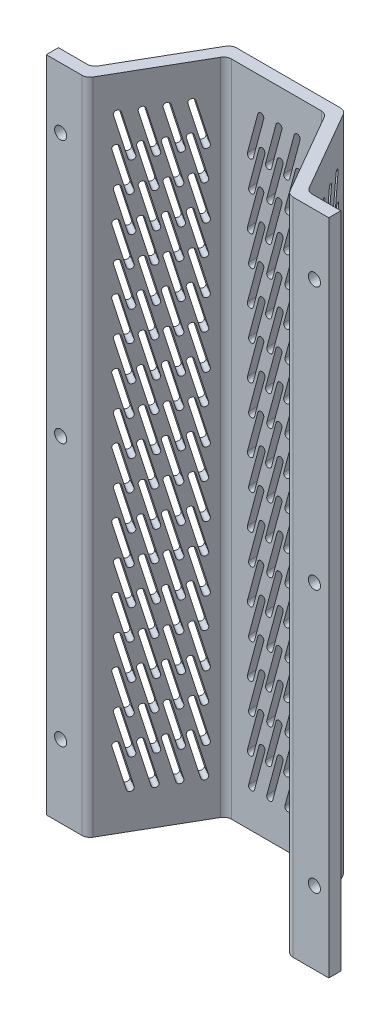
SolidWorks part; units mm, degrees
ref_plane "Front Plane" through (0, 0, 0) normal (0, 0, 1) x (1, 0, 0)
ref_plane "Top Plane" through (0, 0, 0) normal (0, 1, 0) x (1, 0, 0)
ref_plane "Right Plane" through (0, 0, 0) normal (1, 0, 0) x (0, 0, -1)
sketch "Sketch1" plane through (0, 0, 0) normal (0, 1, 0) x (1, 0, 0)
  line L0 (-34.9697, -22) -> (-26.7017, -22)
  line L1 (-26.7017, -22) -> (-14, 0)
  line L2 (-14, 0) -> (14, 0)
  line L3 (14, 0) -> (26.7017, -22)
  line L4 (26.7017, -22) -> (34.9697, -22)
  line L5 (34.9697, -22) -> (34.9697, -25)
  line L6 (34.9697, -25) -> (24.9697, -25)
  line L7 (24.9697, -25) -> (12.2679, -3)
  line L8 (12.2679, -3) -> (-12.2679, -3)
  line L9 (-12.2679, -3) -> (-24.9697, -25)
  line L10 (-24.9697, -25) -> (-34.9697, -25)
  line L11 (-34.9697, -25) -> (-34.9697, -22)
  line L12 (0, 0) -> (0, 7.9784) construction
  point P11 (0, 0)
  dimension "D1" = 3
  dimension "D2" = 3
  dimension "D3" = 3
  dimension "D4" = 120
  dimension "D5" = 28
  dimension "D6" = 25
  dimension "D7" = 10
  dimension "D8" = 10
  dimension "D10" = 25
  dimension "D11" = 3
extrude "Boss-Extrude1" add sketch "Sketch1" along normal blind 163
fillet "Fillet1" radius 2 8 edges at (-24.9697, 81.5, 25) (24.9697, 81.5, 25) (-12.2679, 81.5, 3) (12.2679, 81.5, 3) (26.7017, 81.5, 22) (-26.7017, 81.5, 22) (-14, 81.5, 0) (14, 81.5, 0)
sketch "Sketch2" plane through (0, 0, 0) normal (0, 0, -1) x (-1, 0, 0)
  line L0 (-9.6394, 154.3296) -> (-7.0512, 144.6704) construction
  line L1 (-8.915, 154.5237) -> (-6.3268, 144.8645)
  line L2 (-10.3638, 154.1355) -> (-7.7756, 144.4763)
  line L3 (-12.8453, 163) -> (12.8453, 163) construction
  line L4 (-5.1394, 154.3296) -> (-2.5512, 144.6704) construction
  line L7 (-4.415, 154.5237) -> (-1.8268, 144.8645)
  line L10 (-5.8638, 154.1355) -> (-3.2756, 144.4763)
  line L13 (-0.6394, 154.3296) -> (1.9488, 144.6704) construction
  line L14 (0.085, 154.5237) -> (2.6732, 144.8645)
  line L15 (-1.3638, 154.1355) -> (1.2244, 144.4763)
  line L16 (3.8606, 154.3296) -> (6.4488, 144.6704) construction
  line L17 (4.585, 154.5237) -> (7.1732, 144.8645)
  line L18 (3.1362, 154.1355) -> (5.7244, 144.4763)
  line L19 (-9.6394, 154.3296) -> (-9.6394, 148.3915) construction
  line L20 (-9.9453, 147) -> (-7.3571, 137.3407) construction
  line L21 (-9.2209, 147.1941) -> (-6.6327, 137.5349)
  line L22 (-10.6697, 146.8059) -> (-8.0816, 137.1466)
  line L23 (-5.4453, 147) -> (-2.8571, 137.3407) construction
  line L24 (-4.7209, 147.1941) -> (-2.1327, 137.5349)
  line L25 (-6.1697, 146.8059) -> (-3.5816, 137.1466)
  line L26 (-0.9453, 147) -> (1.6429, 137.3407) construction
  line L27 (-0.2209, 147.1941) -> (2.3673, 137.5349)
  line L28 (-1.6697, 146.8059) -> (0.9184, 137.1466)
  line L29 (3.5547, 147) -> (6.1429, 137.3407) construction
  line L30 (4.2791, 147.1941) -> (6.8673, 137.5349)
  line L31 (2.8303, 146.8059) -> (5.4184, 137.1466)
  line L32 (-9.6394, 138.3296) -> (-9.6394, 132.3915) construction
  line L33 (-9.6394, 138.3296) -> (-7.0512, 128.6704) construction
  line L34 (-8.915, 138.5237) -> (-6.3268, 128.8645)
  line L35 (-10.3638, 138.1355) -> (-7.7756, 128.4763)
  line L36 (-5.1394, 138.3296) -> (-2.5512, 128.6704) construction
  line L37 (-4.415, 138.5237) -> (-1.8268, 128.8645)
  line L38 (-5.8638, 138.1355) -> (-3.2756, 128.4763)
  line L39 (-0.6394, 138.3296) -> (1.9488, 128.6704) construction
  line L40 (0.085, 138.5237) -> (2.6732, 128.8645)
  line L41 (-1.3638, 138.1355) -> (1.2244, 128.4763)
  line L42 (3.8606, 138.3296) -> (6.4488, 128.6704) construction
  line L43 (4.585, 138.5237) -> (7.1732, 128.8645)
  line L44 (3.1362, 138.1355) -> (5.7244, 128.4763)
  line L45 (-9.9453, 131) -> (-7.3571, 121.3407) construction
  line L46 (-9.2209, 131.1941) -> (-6.6327, 121.5349)
  line L47 (-10.6697, 130.8059) -> (-8.0816, 121.1466)
  line L48 (-5.4453, 131) -> (-2.8571, 121.3407) construction
  line L49 (-4.7209, 131.1941) -> (-2.1327, 121.5349)
  line L50 (-6.1697, 130.8059) -> (-3.5816, 121.1466)
  line L51 (-0.9453, 131) -> (1.6429, 121.3407) construction
  line L52 (-0.2209, 131.1941) -> (2.3673, 121.5349)
  line L53 (-1.6697, 130.8059) -> (0.9184, 121.1466)
  line L54 (3.5547, 131) -> (6.1429, 121.3407) construction
  line L55 (4.2791, 131.1941) -> (6.8673, 121.5349)
  line L56 (2.8303, 130.8059) -> (5.4184, 121.1466)
  line L57 (-9.6394, 122.3296) -> (-9.6394, 116.3915) construction
  line L58 (-9.6394, 122.3296) -> (-7.0512, 112.6704) construction
  line L59 (-8.915, 122.5237) -> (-6.3268, 112.8645)
  line L60 (-10.3638, 122.1355) -> (-7.7756, 112.4763)
  line L61 (-5.1394, 122.3296) -> (-2.5512, 112.6704) construction
  line L62 (-4.415, 122.5237) -> (-1.8268, 112.8645)
  line L63 (-5.8638, 122.1355) -> (-3.2756, 112.4763)
  line L64 (-0.6394, 122.3296) -> (1.9488, 112.6704) construction
  line L65 (0.085, 122.5237) -> (2.6732, 112.8645)
  line L66 (-1.3638, 122.1355) -> (1.2244, 112.4763)
  line L67 (3.8606, 122.3296) -> (6.4488, 112.6704) construction
  line L68 (4.585, 122.5237) -> (7.1732, 112.8645)
  line L69 (3.1362, 122.1355) -> (5.7244, 112.4763)
  line L70 (-9.9453, 115) -> (-7.3571, 105.3407) construction
  line L71 (-9.2209, 115.1941) -> (-6.6327, 105.5349)
  line L72 (-10.6697, 114.8059) -> (-8.0816, 105.1466)
  line L73 (-5.4453, 115) -> (-2.8571, 105.3407) construction
  line L74 (-4.7209, 115.1941) -> (-2.1327, 105.5349)
  line L75 (-6.1697, 114.8059) -> (-3.5816, 105.1466)
  line L76 (-0.9453, 115) -> (1.6429, 105.3407) construction
  line L77 (-0.2209, 115.1941) -> (2.3673, 105.5349)
  line L78 (-1.6697, 114.8059) -> (0.9184, 105.1466)
  line L79 (3.5547, 115) -> (6.1429, 105.3407) construction
  line L80 (4.2791, 115.1941) -> (6.8673, 105.5349)
  line L81 (2.8303, 114.8059) -> (5.4184, 105.1466)
  line L82 (-9.6394, 106.3296) -> (-9.6394, 100.3915) construction
  line L83 (-9.6394, 106.3296) -> (-7.0512, 96.6704) construction
  line L84 (-8.915, 106.5237) -> (-6.3268, 96.8645)
  line L85 (-10.3638, 106.1355) -> (-7.7756, 96.4763)
  line L86 (-5.1394, 106.3296) -> (-2.5512, 96.6704) construction
  line L87 (-4.415, 106.5237) -> (-1.8268, 96.8645)
  line L88 (-5.8638, 106.1355) -> (-3.2756, 96.4763)
  line L89 (-0.6394, 106.3296) -> (1.9488, 96.6704) construction
  line L90 (0.085, 106.5237) -> (2.6732, 96.8645)
  line L91 (-1.3638, 106.1355) -> (1.2244, 96.4763)
  line L92 (3.8606, 106.3296) -> (6.4488, 96.6704) construction
  line L93 (4.585, 106.5237) -> (7.1732, 96.8645)
  line L94 (3.1362, 106.1355) -> (5.7244, 96.4763)
  line L95 (-9.9453, 99) -> (-7.3571, 89.3407) construction
  line L96 (-9.2209, 99.1941) -> (-6.6327, 89.5349)
  line L97 (-10.6697, 98.8059) -> (-8.0816, 89.1466)
  line L98 (-5.4453, 99) -> (-2.8571, 89.3407) construction
  line L99 (-4.7209, 99.1941) -> (-2.1327, 89.5349)
  line L100 (-6.1697, 98.8059) -> (-3.5816, 89.1466)
  line L101 (-0.9453, 99) -> (1.6429, 89.3407) construction
  line L102 (-0.2209, 99.1941) -> (2.3673, 89.5349)
  line L103 (-1.6697, 98.8059) -> (0.9184, 89.1466)
  line L104 (3.5547, 99) -> (6.1429, 89.3407) construction
  line L105 (4.2791, 99.1941) -> (6.8673, 89.5349)
  line L106 (2.8303, 98.8059) -> (5.4184, 89.1466)
  line L107 (-9.6394, 90.3296) -> (-9.6394, 84.3915) construction
  line L108 (-9.6394, 90.3296) -> (-7.0512, 80.6704) construction
  line L109 (-8.915, 90.5237) -> (-6.3268, 80.8645)
  line L110 (-10.3638, 90.1355) -> (-7.7756, 80.4763)
  line L111 (-5.1394, 90.3296) -> (-2.5512, 80.6704) construction
  line L112 (-4.415, 90.5237) -> (-1.8268, 80.8645)
  line L113 (-5.8638, 90.1355) -> (-3.2756, 80.4763)
  line L114 (-0.6394, 90.3296) -> (1.9488, 80.6704) construction
  line L115 (0.085, 90.5237) -> (2.6732, 80.8645)
  line L116 (-1.3638, 90.1355) -> (1.2244, 80.4763)
  line L117 (3.8606, 90.3296) -> (6.4488, 80.6704) construction
  line L118 (4.585, 90.5237) -> (7.1732, 80.8645)
  line L119 (3.1362, 90.1355) -> (5.7244, 80.4763)
  line L120 (-9.9453, 83) -> (-7.3571, 73.3407) construction
  line L121 (-9.2209, 83.1941) -> (-6.6327, 73.5349)
  line L122 (-10.6697, 82.8059) -> (-8.0816, 73.1466)
  line L123 (-5.4453, 83) -> (-2.8571, 73.3407) construction
  line L124 (-4.7209, 83.1941) -> (-2.1327, 73.5349)
  line L125 (-6.1697, 82.8059) -> (-3.5816, 73.1466)
  line L126 (-0.9453, 83) -> (1.6429, 73.3407) construction
  line L127 (-0.2209, 83.1941) -> (2.3673, 73.5349)
  line L128 (-1.6697, 82.8059) -> (0.9184, 73.1466)
  line L129 (3.5547, 83) -> (6.1429, 73.3407) construction
  line L130 (4.2791, 83.1941) -> (6.8673, 73.5349)
  line L131 (2.8303, 82.8059) -> (5.4184, 73.1466)
  line L132 (-9.6394, 74.3296) -> (-9.6394, 68.3915) construction
  line L133 (-9.6394, 74.3296) -> (-7.0512, 64.6704) construction
  line L134 (-8.915, 74.5237) -> (-6.3268, 64.8645)
  line L135 (-10.3638, 74.1355) -> (-7.7756, 64.4763)
  line L136 (-5.1394, 74.3296) -> (-2.5512, 64.6704) construction
  line L137 (-4.415, 74.5237) -> (-1.8268, 64.8645)
  line L138 (-5.8638, 74.1355) -> (-3.2756, 64.4763)
  line L139 (-0.6394, 74.3296) -> (1.9488, 64.6704) construction
  line L140 (0.085, 74.5237) -> (2.6732, 64.8645)
  line L141 (-1.3638, 74.1355) -> (1.2244, 64.4763)
  line L142 (3.8606, 74.3296) -> (6.4488, 64.6704) construction
  line L143 (4.585, 74.5237) -> (7.1732, 64.8645)
  line L144 (3.1362, 74.1355) -> (5.7244, 64.4763)
  line L145 (-9.9453, 67) -> (-7.3571, 57.3407) construction
  line L146 (-9.2209, 67.1941) -> (-6.6327, 57.5349)
  line L147 (-10.6697, 66.8059) -> (-8.0816, 57.1466)
  line L148 (-5.4453, 67) -> (-2.8571, 57.3407) construction
  line L149 (-4.7209, 67.1941) -> (-2.1327, 57.5349)
  line L150 (-6.1697, 66.8059) -> (-3.5816, 57.1466)
  line L151 (-0.9453, 67) -> (1.6429, 57.3407) construction
  line L152 (-0.2209, 67.1941) -> (2.3673, 57.5349)
  line L153 (-1.6697, 66.8059) -> (0.9184, 57.1466)
  line L154 (3.5547, 67) -> (6.1429, 57.3407) construction
  line L155 (4.2791, 67.1941) -> (6.8673, 57.5349)
  line L156 (2.8303, 66.8059) -> (5.4184, 57.1466)
  line L157 (-9.6394, 58.3296) -> (-9.6394, 52.3915) construction
  line L158 (-9.6394, 58.3296) -> (-7.0512, 48.6704) construction
  line L159 (-8.915, 58.5237) -> (-6.3268, 48.8645)
  line L160 (-10.3638, 58.1355) -> (-7.7756, 48.4763)
  line L161 (-5.1394, 58.3296) -> (-2.5512, 48.6704) construction
  line L162 (-4.415, 58.5237) -> (-1.8268, 48.8645)
  line L163 (-5.8638, 58.1355) -> (-3.2756, 48.4763)
  line L164 (-0.6394, 58.3296) -> (1.9488, 48.6704) construction
  line L165 (0.085, 58.5237) -> (2.6732, 48.8645)
  line L166 (-1.3638, 58.1355) -> (1.2244, 48.4763)
  line L167 (3.8606, 58.3296) -> (6.4488, 48.6704) construction
  line L168 (4.585, 58.5237) -> (7.1732, 48.8645)
  line L169 (3.1362, 58.1355) -> (5.7244, 48.4763)
  line L170 (-9.9453, 51) -> (-7.3571, 41.3407) construction
  line L171 (-9.2209, 51.1941) -> (-6.6327, 41.5349)
  line L172 (-10.6697, 50.8059) -> (-8.0816, 41.1466)
  line L173 (-5.4453, 51) -> (-2.8571, 41.3407) construction
  line L174 (-4.7209, 51.1941) -> (-2.1327, 41.5349)
  line L175 (-6.1697, 50.8059) -> (-3.5816, 41.1466)
  line L176 (-0.9453, 51) -> (1.6429, 41.3407) construction
  line L177 (-0.2209, 51.1941) -> (2.3673, 41.5349)
  line L178 (-1.6697, 50.8059) -> (0.9184, 41.1466)
  line L179 (3.5547, 51) -> (6.1429, 41.3407) construction
  line L180 (4.2791, 51.1941) -> (6.8673, 41.5349)
  line L181 (2.8303, 50.8059) -> (5.4184, 41.1466)
  line L182 (-9.6394, 42.3296) -> (-9.6394, 36.3915) construction
  line L183 (-9.6394, 42.3296) -> (-7.0512, 32.6704) construction
  line L184 (-8.915, 42.5237) -> (-6.3268, 32.8645)
  line L185 (-10.3638, 42.1355) -> (-7.7756, 32.4763)
  line L186 (-5.1394, 42.3296) -> (-2.5512, 32.6704) construction
  line L187 (-4.415, 42.5237) -> (-1.8268, 32.8645)
  line L188 (-5.8638, 42.1355) -> (-3.2756, 32.4763)
  line L189 (-0.6394, 42.3296) -> (1.9488, 32.6704) construction
  line L190 (0.085, 42.5237) -> (2.6732, 32.8645)
  line L191 (-1.3638, 42.1355) -> (1.2244, 32.4763)
  line L192 (3.8606, 42.3296) -> (6.4488, 32.6704) construction
  line L193 (4.585, 42.5237) -> (7.1732, 32.8645)
  line L194 (3.1362, 42.1355) -> (5.7244, 32.4763)
  line L195 (-9.9453, 35) -> (-7.3571, 25.3407) construction
  line L196 (-9.2209, 35.1941) -> (-6.6327, 25.5349)
  line L197 (-10.6697, 34.8059) -> (-8.0816, 25.1466)
  line L198 (-5.4453, 35) -> (-2.8571, 25.3407) construction
  line L199 (-4.7209, 35.1941) -> (-2.1327, 25.5349)
  line L200 (-6.1697, 34.8059) -> (-3.5816, 25.1466)
  line L201 (-0.9453, 35) -> (1.6429, 25.3407) construction
  line L202 (-0.2209, 35.1941) -> (2.3673, 25.5349)
  line L203 (-1.6697, 34.8059) -> (0.9184, 25.1466)
  line L204 (3.5547, 35) -> (6.1429, 25.3407) construction
  line L205 (4.2791, 35.1941) -> (6.8673, 25.5349)
  line L206 (2.8303, 34.8059) -> (5.4184, 25.1466)
  line L207 (-9.6394, 26.3296) -> (-9.6394, 20.3915) construction
  line L208 (-9.6394, 26.3296) -> (-7.0512, 16.6704) construction
  line L209 (-8.915, 26.5237) -> (-6.3268, 16.8645)
  line L210 (-10.3638, 26.1355) -> (-7.7756, 16.4763)
  line L211 (-5.1394, 26.3296) -> (-2.5512, 16.6704) construction
  line L212 (-4.415, 26.5237) -> (-1.8268, 16.8645)
  line L213 (-5.8638, 26.1355) -> (-3.2756, 16.4763)
  line L214 (-0.6394, 26.3296) -> (1.9488, 16.6704) construction
  line L215 (0.085, 26.5237) -> (2.6732, 16.8645)
  line L216 (-1.3638, 26.1355) -> (1.2244, 16.4763)
  line L217 (3.8606, 26.3296) -> (6.4488, 16.6704) construction
  line L218 (4.585, 26.5237) -> (7.1732, 16.8645)
  line L219 (3.1362, 26.1355) -> (5.7244, 16.4763)
  line L220 (-9.9453, 19) -> (-7.3571, 9.3407) construction
  line L221 (-9.2209, 19.1941) -> (-6.6327, 9.5349)
  line L222 (-10.6697, 18.8059) -> (-8.0816, 9.1466)
  line L223 (-5.4453, 19) -> (-2.8571, 9.3407) construction
  line L224 (-4.7209, 19.1941) -> (-2.1327, 9.5349)
  line L225 (-6.1697, 18.8059) -> (-3.5816, 9.1466)
  line L226 (-0.9453, 19) -> (1.6429, 9.3407) construction
  line L227 (-0.2209, 19.1941) -> (2.3673, 9.5349)
  line L228 (-1.6697, 18.8059) -> (0.9184, 9.1466)
  line L229 (3.5547, 19) -> (6.1429, 9.3407) construction
  line L230 (4.2791, 19.1941) -> (6.8673, 9.5349)
  line L231 (2.8303, 18.8059) -> (5.4184, 9.1466)
  line L233 (-12.8453, 163) -> (-12.8453, 0) construction
  arc A0 (-8.915, 154.5237) -> (-10.3638, 154.1355) centre (-9.6394, 154.3296) ccw
  arc A1 (-7.7756, 144.4763) -> (-6.3268, 144.8645) centre (-7.0512, 144.6704) ccw
  arc A8 (-4.415, 154.5237) -> (-5.8638, 154.1355) centre (-5.1394, 154.3296) ccw
  arc A9 (-3.2756, 144.4763) -> (-1.8268, 144.8645) centre (-2.5512, 144.6704) ccw
  arc A10 (0.085, 154.5237) -> (-1.3638, 154.1355) centre (-0.6394, 154.3296) ccw
  arc A11 (1.2244, 144.4763) -> (2.6732, 144.8645) centre (1.9488, 144.6704) ccw
  arc A12 (4.585, 154.5237) -> (3.1362, 154.1355) centre (3.8606, 154.3296) ccw
  arc A13 (5.7244, 144.4763) -> (7.1732, 144.8645) centre (6.4488, 144.6704) ccw
  arc A14 (-9.2209, 147.1941) -> (-10.6697, 146.8059) centre (-9.9453, 147) ccw
  arc A15 (-8.0816, 137.1466) -> (-6.6327, 137.5349) centre (-7.3571, 137.3407) ccw
  arc A16 (-4.7209, 147.1941) -> (-6.1697, 146.8059) centre (-5.4453, 147) ccw
  arc A17 (-3.5816, 137.1466) -> (-2.1327, 137.5349) centre (-2.8571, 137.3407) ccw
  arc A18 (-0.2209, 147.1941) -> (-1.6697, 146.8059) centre (-0.9453, 147) ccw
  arc A19 (0.9184, 137.1466) -> (2.3673, 137.5349) centre (1.6429, 137.3407) ccw
  arc A20 (4.2791, 147.1941) -> (2.8303, 146.8059) centre (3.5547, 147) ccw
  arc A21 (5.4184, 137.1466) -> (6.8673, 137.5349) centre (6.1429, 137.3407) ccw
  arc A22 (-8.915, 138.5237) -> (-10.3638, 138.1355) centre (-9.6394, 138.3296) ccw
  arc A23 (-7.7756, 128.4763) -> (-6.3268, 128.8645) centre (-7.0512, 128.6704) ccw
  arc A24 (-4.415, 138.5237) -> (-5.8638, 138.1355) centre (-5.1394, 138.3296) ccw
  arc A25 (-3.2756, 128.4763) -> (-1.8268, 128.8645) centre (-2.5512, 128.6704) ccw
  arc A26 (0.085, 138.5237) -> (-1.3638, 138.1355) centre (-0.6394, 138.3296) ccw
  arc A27 (1.2244, 128.4763) -> (2.6732, 128.8645) centre (1.9488, 128.6704) ccw
  arc A28 (4.585, 138.5237) -> (3.1362, 138.1355) centre (3.8606, 138.3296) ccw
  arc A29 (5.7244, 128.4763) -> (7.1732, 128.8645) centre (6.4488, 128.6704) ccw
  arc A30 (-9.2209, 131.1941) -> (-10.6697, 130.8059) centre (-9.9453, 131) ccw
  arc A31 (-8.0816, 121.1466) -> (-6.6327, 121.5349) centre (-7.3571, 121.3407) ccw
  arc A32 (-4.7209, 131.1941) -> (-6.1697, 130.8059) centre (-5.4453, 131) ccw
  arc A33 (-3.5816, 121.1466) -> (-2.1327, 121.5349) centre (-2.8571, 121.3407) ccw
  arc A34 (-0.2209, 131.1941) -> (-1.6697, 130.8059) centre (-0.9453, 131) ccw
  arc A35 (0.9184, 121.1466) -> (2.3673, 121.5349) centre (1.6429, 121.3407) ccw
  arc A36 (4.2791, 131.1941) -> (2.8303, 130.8059) centre (3.5547, 131) ccw
  arc A37 (5.4184, 121.1466) -> (6.8673, 121.5349) centre (6.1429, 121.3407) ccw
  arc A38 (-8.915, 122.5237) -> (-10.3638, 122.1355) centre (-9.6394, 122.3296) ccw
  arc A39 (-7.7756, 112.4763) -> (-6.3268, 112.8645) centre (-7.0512, 112.6704) ccw
  arc A40 (-4.415, 122.5237) -> (-5.8638, 122.1355) centre (-5.1394, 122.3296) ccw
  arc A41 (-3.2756, 112.4763) -> (-1.8268, 112.8645) centre (-2.5512, 112.6704) ccw
  arc A42 (0.085, 122.5237) -> (-1.3638, 122.1355) centre (-0.6394, 122.3296) ccw
  arc A43 (1.2244, 112.4763) -> (2.6732, 112.8645) centre (1.9488, 112.6704) ccw
  arc A44 (4.585, 122.5237) -> (3.1362, 122.1355) centre (3.8606, 122.3296) ccw
  arc A45 (5.7244, 112.4763) -> (7.1732, 112.8645) centre (6.4488, 112.6704) ccw
  arc A46 (-9.2209, 115.1941) -> (-10.6697, 114.8059) centre (-9.9453, 115) ccw
  arc A47 (-8.0816, 105.1466) -> (-6.6327, 105.5349) centre (-7.3571, 105.3407) ccw
  arc A48 (-4.7209, 115.1941) -> (-6.1697, 114.8059) centre (-5.4453, 115) ccw
  arc A49 (-3.5816, 105.1466) -> (-2.1327, 105.5349) centre (-2.8571, 105.3407) ccw
  arc A50 (-0.2209, 115.1941) -> (-1.6697, 114.8059) centre (-0.9453, 115) ccw
  arc A51 (0.9184, 105.1466) -> (2.3673, 105.5349) centre (1.6429, 105.3407) ccw
  arc A52 (4.2791, 115.1941) -> (2.8303, 114.8059) centre (3.5547, 115) ccw
  arc A53 (5.4184, 105.1466) -> (6.8673, 105.5349) centre (6.1429, 105.3407) ccw
  arc A54 (-8.915, 106.5237) -> (-10.3638, 106.1355) centre (-9.6394, 106.3296) ccw
  arc A55 (-7.7756, 96.4763) -> (-6.3268, 96.8645) centre (-7.0512, 96.6704) ccw
  arc A56 (-4.415, 106.5237) -> (-5.8638, 106.1355) centre (-5.1394, 106.3296) ccw
  arc A57 (-3.2756, 96.4763) -> (-1.8268, 96.8645) centre (-2.5512, 96.6704) ccw
  arc A58 (0.085, 106.5237) -> (-1.3638, 106.1355) centre (-0.6394, 106.3296) ccw
  arc A59 (1.2244, 96.4763) -> (2.6732, 96.8645) centre (1.9488, 96.6704) ccw
  arc A60 (4.585, 106.5237) -> (3.1362, 106.1355) centre (3.8606, 106.3296) ccw
  arc A61 (5.7244, 96.4763) -> (7.1732, 96.8645) centre (6.4488, 96.6704) ccw
  arc A62 (-9.2209, 99.1941) -> (-10.6697, 98.8059) centre (-9.9453, 99) ccw
  arc A63 (-8.0816, 89.1466) -> (-6.6327, 89.5349) centre (-7.3571, 89.3407) ccw
  arc A64 (-4.7209, 99.1941) -> (-6.1697, 98.8059) centre (-5.4453, 99) ccw
  arc A65 (-3.5816, 89.1466) -> (-2.1327, 89.5349) centre (-2.8571, 89.3407) ccw
  arc A66 (-0.2209, 99.1941) -> (-1.6697, 98.8059) centre (-0.9453, 99) ccw
  arc A67 (0.9184, 89.1466) -> (2.3673, 89.5349) centre (1.6429, 89.3407) ccw
  arc A68 (4.2791, 99.1941) -> (2.8303, 98.8059) centre (3.5547, 99) ccw
  arc A69 (5.4184, 89.1466) -> (6.8673, 89.5349) centre (6.1429, 89.3407) ccw
  arc A70 (-8.915, 90.5237) -> (-10.3638, 90.1355) centre (-9.6394, 90.3296) ccw
  arc A71 (-7.7756, 80.4763) -> (-6.3268, 80.8645) centre (-7.0512, 80.6704) ccw
  arc A72 (-4.415, 90.5237) -> (-5.8638, 90.1355) centre (-5.1394, 90.3296) ccw
  arc A73 (-3.2756, 80.4763) -> (-1.8268, 80.8645) centre (-2.5512, 80.6704) ccw
  arc A74 (0.085, 90.5237) -> (-1.3638, 90.1355) centre (-0.6394, 90.3296) ccw
  arc A75 (1.2244, 80.4763) -> (2.6732, 80.8645) centre (1.9488, 80.6704) ccw
  arc A76 (4.585, 90.5237) -> (3.1362, 90.1355) centre (3.8606, 90.3296) ccw
  arc A77 (5.7244, 80.4763) -> (7.1732, 80.8645) centre (6.4488, 80.6704) ccw
  arc A78 (-9.2209, 83.1941) -> (-10.6697, 82.8059) centre (-9.9453, 83) ccw
  arc A79 (-8.0816, 73.1466) -> (-6.6327, 73.5349) centre (-7.3571, 73.3407) ccw
  arc A80 (-4.7209, 83.1941) -> (-6.1697, 82.8059) centre (-5.4453, 83) ccw
  arc A81 (-3.5816, 73.1466) -> (-2.1327, 73.5349) centre (-2.8571, 73.3407) ccw
  arc A82 (-0.2209, 83.1941) -> (-1.6697, 82.8059) centre (-0.9453, 83) ccw
  arc A83 (0.9184, 73.1466) -> (2.3673, 73.5349) centre (1.6429, 73.3407) ccw
  arc A84 (4.2791, 83.1941) -> (2.8303, 82.8059) centre (3.5547, 83) ccw
  arc A85 (5.4184, 73.1466) -> (6.8673, 73.5349) centre (6.1429, 73.3407) ccw
  arc A86 (-8.915, 74.5237) -> (-10.3638, 74.1355) centre (-9.6394, 74.3296) ccw
  arc A87 (-7.7756, 64.4763) -> (-6.3268, 64.8645) centre (-7.0512, 64.6704) ccw
  arc A88 (-4.415, 74.5237) -> (-5.8638, 74.1355) centre (-5.1394, 74.3296) ccw
  arc A89 (-3.2756, 64.4763) -> (-1.8268, 64.8645) centre (-2.5512, 64.6704) ccw
  arc A90 (0.085, 74.5237) -> (-1.3638, 74.1355) centre (-0.6394, 74.3296) ccw
  arc A91 (1.2244, 64.4763) -> (2.6732, 64.8645) centre (1.9488, 64.6704) ccw
  arc A92 (4.585, 74.5237) -> (3.1362, 74.1355) centre (3.8606, 74.3296) ccw
  arc A93 (5.7244, 64.4763) -> (7.1732, 64.8645) centre (6.4488, 64.6704) ccw
  arc A94 (-9.2209, 67.1941) -> (-10.6697, 66.8059) centre (-9.9453, 67) ccw
  arc A95 (-8.0816, 57.1466) -> (-6.6327, 57.5349) centre (-7.3571, 57.3407) ccw
  arc A96 (-4.7209, 67.1941) -> (-6.1697, 66.8059) centre (-5.4453, 67) ccw
  arc A97 (-3.5816, 57.1466) -> (-2.1327, 57.5349) centre (-2.8571, 57.3407) ccw
  arc A98 (-0.2209, 67.1941) -> (-1.6697, 66.8059) centre (-0.9453, 67) ccw
  arc A99 (0.9184, 57.1466) -> (2.3673, 57.5349) centre (1.6429, 57.3407) ccw
  arc A100 (4.2791, 67.1941) -> (2.8303, 66.8059) centre (3.5547, 67) ccw
  arc A101 (5.4184, 57.1466) -> (6.8673, 57.5349) centre (6.1429, 57.3407) ccw
  arc A102 (-8.915, 58.5237) -> (-10.3638, 58.1355) centre (-9.6394, 58.3296) ccw
  arc A103 (-7.7756, 48.4763) -> (-6.3268, 48.8645) centre (-7.0512, 48.6704) ccw
  arc A104 (-4.415, 58.5237) -> (-5.8638, 58.1355) centre (-5.1394, 58.3296) ccw
  arc A105 (-3.2756, 48.4763) -> (-1.8268, 48.8645) centre (-2.5512, 48.6704) ccw
  arc A106 (0.085, 58.5237) -> (-1.3638, 58.1355) centre (-0.6394, 58.3296) ccw
  arc A107 (1.2244, 48.4763) -> (2.6732, 48.8645) centre (1.9488, 48.6704) ccw
  arc A108 (4.585, 58.5237) -> (3.1362, 58.1355) centre (3.8606, 58.3296) ccw
  arc A109 (5.7244, 48.4763) -> (7.1732, 48.8645) centre (6.4488, 48.6704) ccw
  arc A110 (-9.2209, 51.1941) -> (-10.6697, 50.8059) centre (-9.9453, 51) ccw
  arc A111 (-8.0816, 41.1466) -> (-6.6327, 41.5349) centre (-7.3571, 41.3407) ccw
  arc A112 (-4.7209, 51.1941) -> (-6.1697, 50.8059) centre (-5.4453, 51) ccw
  arc A113 (-3.5816, 41.1466) -> (-2.1327, 41.5349) centre (-2.8571, 41.3407) ccw
  arc A114 (-0.2209, 51.1941) -> (-1.6697, 50.8059) centre (-0.9453, 51) ccw
  arc A115 (0.9184, 41.1466) -> (2.3673, 41.5349) centre (1.6429, 41.3407) ccw
  arc A116 (4.2791, 51.1941) -> (2.8303, 50.8059) centre (3.5547, 51) ccw
  arc A117 (5.4184, 41.1466) -> (6.8673, 41.5349) centre (6.1429, 41.3407) ccw
  arc A118 (-8.915, 42.5237) -> (-10.3638, 42.1355) centre (-9.6394, 42.3296) ccw
  arc A119 (-7.7756, 32.4763) -> (-6.3268, 32.8645) centre (-7.0512, 32.6704) ccw
  arc A120 (-4.415, 42.5237) -> (-5.8638, 42.1355) centre (-5.1394, 42.3296) ccw
  arc A121 (-3.2756, 32.4763) -> (-1.8268, 32.8645) centre (-2.5512, 32.6704) ccw
  arc A122 (0.085, 42.5237) -> (-1.3638, 42.1355) centre (-0.6394, 42.3296) ccw
  arc A123 (1.2244, 32.4763) -> (2.6732, 32.8645) centre (1.9488, 32.6704) ccw
  arc A124 (4.585, 42.5237) -> (3.1362, 42.1355) centre (3.8606, 42.3296) ccw
  arc A125 (5.7244, 32.4763) -> (7.1732, 32.8645) centre (6.4488, 32.6704) ccw
  arc A126 (-9.2209, 35.1941) -> (-10.6697, 34.8059) centre (-9.9453, 35) ccw
  arc A127 (-8.0816, 25.1466) -> (-6.6327, 25.5349) centre (-7.3571, 25.3407) ccw
  arc A128 (-4.7209, 35.1941) -> (-6.1697, 34.8059) centre (-5.4453, 35) ccw
  arc A129 (-3.5816, 25.1466) -> (-2.1327, 25.5349) centre (-2.8571, 25.3407) ccw
  arc A130 (-0.2209, 35.1941) -> (-1.6697, 34.8059) centre (-0.9453, 35) ccw
  arc A131 (0.9184, 25.1466) -> (2.3673, 25.5349) centre (1.6429, 25.3407) ccw
  arc A132 (4.2791, 35.1941) -> (2.8303, 34.8059) centre (3.5547, 35) ccw
  arc A133 (5.4184, 25.1466) -> (6.8673, 25.5349) centre (6.1429, 25.3407) ccw
  arc A134 (-8.915, 26.5237) -> (-10.3638, 26.1355) centre (-9.6394, 26.3296) ccw
  arc A135 (-7.7756, 16.4763) -> (-6.3268, 16.8645) centre (-7.0512, 16.6704) ccw
  arc A136 (-4.415, 26.5237) -> (-5.8638, 26.1355) centre (-5.1394, 26.3296) ccw
  arc A137 (-3.2756, 16.4763) -> (-1.8268, 16.8645) centre (-2.5512, 16.6704) ccw
  arc A138 (0.085, 26.5237) -> (-1.3638, 26.1355) centre (-0.6394, 26.3296) ccw
  arc A139 (1.2244, 16.4763) -> (2.6732, 16.8645) centre (1.9488, 16.6704) ccw
  arc A140 (4.585, 26.5237) -> (3.1362, 26.1355) centre (3.8606, 26.3296) ccw
  arc A141 (5.7244, 16.4763) -> (7.1732, 16.8645) centre (6.4488, 16.6704) ccw
  arc A142 (-9.2209, 19.1941) -> (-10.6697, 18.8059) centre (-9.9453, 19) ccw
  arc A143 (-8.0816, 9.1466) -> (-6.6327, 9.5349) centre (-7.3571, 9.3407) ccw
  arc A144 (-4.7209, 19.1941) -> (-6.1697, 18.8059) centre (-5.4453, 19) ccw
  arc A145 (-3.5816, 9.1466) -> (-2.1327, 9.5349) centre (-2.8571, 9.3407) ccw
  arc A146 (-0.2209, 19.1941) -> (-1.6697, 18.8059) centre (-0.9453, 19) ccw
  arc A147 (0.9184, 9.1466) -> (2.3673, 9.5349) centre (1.6429, 9.3407) ccw
  arc A148 (4.2791, 19.1941) -> (2.8303, 18.8059) centre (3.5547, 19) ccw
  arc A149 (5.4184, 9.1466) -> (6.8673, 9.5349) centre (6.1429, 9.3407) ccw
  point P2 (-8.3453, 149.5)
  point P14 (-3.8453, 149.5)
  point P21 (0.6547, 149.5)
  point P28 (5.1547, 149.5)
  point P35 (-8.6512, 142.1704)
  point P44 (-4.1512, 142.1704)
  point P51 (0.3488, 142.1704)
  point P58 (4.8488, 142.1704)
  point P65 (-8.3453, 133.5)
  point P74 (-3.8453, 133.5)
  point P81 (0.6547, 133.5)
  point P88 (5.1547, 133.5)
  point P95 (-8.6512, 126.1704)
  point P102 (-4.1512, 126.1704)
  point P109 (0.3488, 126.1704)
  point P116 (4.8488, 126.1704)
  point P123 (-8.3453, 117.5)
  point P132 (-3.8453, 117.5)
  point P139 (0.6547, 117.5)
  point P146 (5.1547, 117.5)
  point P153 (-8.6512, 110.1704)
  point P160 (-4.1512, 110.1704)
  point P167 (0.3488, 110.1704)
  point P174 (4.8488, 110.1704)
  point P181 (-8.3453, 101.5)
  point P190 (-3.8453, 101.5)
  point P197 (0.6547, 101.5)
  point P204 (5.1547, 101.5)
  point P211 (-8.6512, 94.1704)
  point P218 (-4.1512, 94.1704)
  point P225 (0.3488, 94.1704)
  point P232 (4.8488, 94.1704)
  point P239 (-8.3453, 85.5)
  point P248 (-3.8453, 85.5)
  point P255 (0.6547, 85.5)
  point P262 (5.1547, 85.5)
  point P269 (-8.6512, 78.1704)
  point P276 (-4.1512, 78.1704)
  point P283 (0.3488, 78.1704)
  point P290 (4.8488, 78.1704)
  point P297 (-8.3453, 69.5)
  point P306 (-3.8453, 69.5)
  point P313 (0.6547, 69.5)
  point P320 (5.1547, 69.5)
  point P327 (-8.6512, 62.1704)
  point P334 (-4.1512, 62.1704)
  point P341 (0.3488, 62.1704)
  point P348 (4.8488, 62.1704)
  point P355 (-8.3453, 53.5)
  point P364 (-3.8453, 53.5)
  point P371 (0.6547, 53.5)
  point P378 (5.1547, 53.5)
  point P385 (-8.6512, 46.1704)
  point P392 (-4.1512, 46.1704)
  point P399 (0.3488, 46.1704)
  point P406 (4.8488, 46.1704)
  point P413 (-8.3453, 37.5)
  point P422 (-3.8453, 37.5)
  point P429 (0.6547, 37.5)
  point P436 (5.1547, 37.5)
  point P443 (-8.6512, 30.1704)
  point P450 (-4.1512, 30.1704)
  point P457 (0.3488, 30.1704)
  point P464 (4.8488, 30.1704)
  point P471 (-8.3453, 21.5)
  point P480 (-3.8453, 21.5)
  point P487 (0.6547, 21.5)
  point P494 (5.1547, 21.5)
  point P501 (-8.6512, 14.1704)
  point P508 (-4.1512, 14.1704)
  point P515 (0.3488, 14.1704)
  point P522 (4.8488, 14.1704)
  dimension "D1" = 10
  dimension "D2" = 1.5
  dimension "D3" = 13.5
  dimension "D4" = 4.5
  dimension "D6" = 15
  dimension "D7" = 10
  dimension "D8" = 1.5
  dimension "D9" = 9
  dimension "D11" = 2.5
  dimension "D12" = 2.9
  dimension "D5" = 4
  dimension "D10" = 4
extrude "Cut-Extrude1" cut sketch "Sketch2" against normal up to surface (3 mm away) up to face at (0, 81.5, 3)
sketch "Sketch5" plane through (6.8914, 0, -12.3125) normal (-0.866, 0, 0.5) x (0.5, 0, 0.866)
  line L0 (19.6719, 153.3105) -> (22.2601, 143.6513) construction
  line L1 (20.3963, 153.5046) -> (22.9845, 143.8454)
  line L2 (18.9474, 153.1164) -> (21.5356, 143.4571)
  line L4 (24.1719, 153.3105) -> (26.7601, 143.6513) construction
  line L7 (24.8963, 153.5046) -> (27.4845, 143.8454)
  line L10 (23.4474, 153.1164) -> (26.0356, 143.4571)
  line L13 (28.6719, 153.3105) -> (31.2601, 143.6513) construction
  line L14 (29.3963, 153.5046) -> (31.9845, 143.8454)
  line L15 (27.9474, 153.1164) -> (30.5356, 143.4571)
  line L16 (33.1719, 153.3105) -> (35.7601, 143.6513) construction
  line L17 (33.8963, 153.5046) -> (36.4845, 143.8454)
  line L18 (32.4474, 153.1164) -> (35.0356, 143.4571)
  line L19 (19.6719, 153.3105) -> (19.6719, 147.4945) construction
  line L20 (19.3719, 145.9809) -> (21.9601, 136.3216) construction
  line L21 (20.0963, 146.175) -> (22.6845, 136.5157)
  line L22 (18.6474, 145.7868) -> (21.2356, 136.1275)
  line L23 (23.8719, 145.9809) -> (26.4601, 136.3216) construction
  line L24 (24.5963, 146.175) -> (27.1845, 136.5157)
  line L25 (23.1474, 145.7868) -> (25.7356, 136.1275)
  line L26 (28.3719, 145.9809) -> (30.9601, 136.3216) construction
  line L27 (29.0963, 146.175) -> (31.6845, 136.5157)
  line L28 (27.6474, 145.7868) -> (30.2356, 136.1275)
  line L29 (32.8719, 145.9809) -> (35.4601, 136.3216) construction
  line L30 (33.5963, 146.175) -> (36.1845, 136.5157)
  line L31 (32.1474, 145.7868) -> (34.7356, 136.1275)
  line L32 (19.6719, 137.3105) -> (19.6719, 131.4945) construction
  line L33 (19.6719, 137.3105) -> (22.2601, 127.6513) construction
  line L34 (20.3963, 137.5046) -> (22.9845, 127.8454)
  line L35 (18.9474, 137.1164) -> (21.5356, 127.4571)
  line L36 (24.1719, 137.3105) -> (26.7601, 127.6513) construction
  line L37 (24.8963, 137.5046) -> (27.4845, 127.8454)
  line L38 (23.4474, 137.1164) -> (26.0356, 127.4571)
  line L39 (28.6719, 137.3105) -> (31.2601, 127.6513) construction
  line L40 (29.3963, 137.5046) -> (31.9845, 127.8454)
  line L41 (27.9474, 137.1164) -> (30.5356, 127.4571)
  line L42 (33.1719, 137.3105) -> (35.7601, 127.6513) construction
  line L43 (33.8963, 137.5046) -> (36.4845, 127.8454)
  line L44 (32.4474, 137.1164) -> (35.0356, 127.4571)
  line L45 (19.3719, 129.9809) -> (21.9601, 120.3216) construction
  line L46 (20.0963, 130.175) -> (22.6845, 120.5157)
  line L47 (18.6474, 129.7868) -> (21.2356, 120.1275)
  line L48 (23.8719, 129.9809) -> (26.4601, 120.3216) construction
  line L49 (24.5963, 130.175) -> (27.1845, 120.5157)
  line L50 (23.1474, 129.7868) -> (25.7356, 120.1275)
  line L51 (28.3719, 129.9809) -> (30.9601, 120.3216) construction
  line L52 (29.0963, 130.175) -> (31.6845, 120.5157)
  line L53 (27.6474, 129.7868) -> (30.2356, 120.1275)
  line L54 (32.8719, 129.9809) -> (35.4601, 120.3216) construction
  line L55 (33.5963, 130.175) -> (36.1845, 120.5157)
  line L56 (32.1474, 129.7868) -> (34.7356, 120.1275)
  line L57 (19.6719, 121.3105) -> (19.6719, 115.4945) construction
  line L58 (19.6719, 121.3105) -> (22.2601, 111.6513) construction
  line L59 (20.3963, 121.5046) -> (22.9845, 111.8454)
  line L60 (18.9474, 121.1164) -> (21.5356, 111.4571)
  line L61 (24.1719, 121.3105) -> (26.7601, 111.6513) construction
  line L62 (24.8963, 121.5046) -> (27.4845, 111.8454)
  line L63 (23.4474, 121.1164) -> (26.0356, 111.4571)
  line L64 (28.6719, 121.3105) -> (31.2601, 111.6513) construction
  line L65 (29.3963, 121.5046) -> (31.9845, 111.8454)
  line L66 (27.9474, 121.1164) -> (30.5356, 111.4571)
  line L67 (33.1719, 121.3105) -> (35.7601, 111.6513) construction
  line L68 (33.8963, 121.5046) -> (36.4845, 111.8454)
  line L69 (32.4474, 121.1164) -> (35.0356, 111.4571)
  line L70 (19.3719, 113.9809) -> (21.9601, 104.3216) construction
  line L71 (20.0963, 114.175) -> (22.6845, 104.5157)
  line L72 (18.6474, 113.7868) -> (21.2356, 104.1275)
  line L73 (23.8719, 113.9809) -> (26.4601, 104.3216) construction
  line L74 (24.5963, 114.175) -> (27.1845, 104.5157)
  line L75 (23.1474, 113.7868) -> (25.7356, 104.1275)
  line L76 (28.3719, 113.9809) -> (30.9601, 104.3216) construction
  line L77 (29.0963, 114.175) -> (31.6845, 104.5157)
  line L78 (27.6474, 113.7868) -> (30.2356, 104.1275)
  line L79 (32.8719, 113.9809) -> (35.4601, 104.3216) construction
  line L80 (33.5963, 114.175) -> (36.1845, 104.5157)
  line L81 (32.1474, 113.7868) -> (34.7356, 104.1275)
  line L82 (19.6719, 105.3105) -> (19.6719, 99.4945) construction
  line L83 (19.6719, 105.3105) -> (22.2601, 95.6513) construction
  line L84 (20.3963, 105.5046) -> (22.9845, 95.8454)
  line L85 (18.9474, 105.1164) -> (21.5356, 95.4571)
  line L86 (24.1719, 105.3105) -> (26.7601, 95.6513) construction
  line L87 (24.8963, 105.5046) -> (27.4845, 95.8454)
  line L88 (23.4474, 105.1164) -> (26.0356, 95.4571)
  line L89 (28.6719, 105.3105) -> (31.2601, 95.6513) construction
  line L90 (29.3963, 105.5046) -> (31.9845, 95.8454)
  line L91 (27.9474, 105.1164) -> (30.5356, 95.4571)
  line L92 (33.1719, 105.3105) -> (35.7601, 95.6513) construction
  line L93 (33.8963, 105.5046) -> (36.4845, 95.8454)
  line L94 (32.4474, 105.1164) -> (35.0356, 95.4571)
  line L95 (19.3719, 97.9809) -> (21.9601, 88.3216) construction
  line L96 (20.0963, 98.175) -> (22.6845, 88.5157)
  line L97 (18.6474, 97.7868) -> (21.2356, 88.1275)
  line L98 (23.8719, 97.9809) -> (26.4601, 88.3216) construction
  line L99 (24.5963, 98.175) -> (27.1845, 88.5157)
  line L100 (23.1474, 97.7868) -> (25.7356, 88.1275)
  line L101 (28.3719, 97.9809) -> (30.9601, 88.3216) construction
  line L102 (29.0963, 98.175) -> (31.6845, 88.5157)
  line L103 (27.6474, 97.7868) -> (30.2356, 88.1275)
  line L104 (32.8719, 97.9809) -> (35.4601, 88.3216) construction
  line L105 (33.5963, 98.175) -> (36.1845, 88.5157)
  line L106 (32.1474, 97.7868) -> (34.7356, 88.1275)
  line L107 (19.6719, 89.3105) -> (19.6719, 83.4945) construction
  line L108 (19.6719, 89.3105) -> (22.2601, 79.6513) construction
  line L109 (20.3963, 89.5046) -> (22.9845, 79.8454)
  line L110 (18.9474, 89.1164) -> (21.5356, 79.4571)
  line L111 (24.1719, 89.3105) -> (26.7601, 79.6513) construction
  line L112 (24.8963, 89.5046) -> (27.4845, 79.8454)
  line L113 (23.4474, 89.1164) -> (26.0356, 79.4571)
  line L114 (28.6719, 89.3105) -> (31.2601, 79.6513) construction
  line L115 (29.3963, 89.5046) -> (31.9845, 79.8454)
  line L116 (27.9474, 89.1164) -> (30.5356, 79.4571)
  line L117 (33.1719, 89.3105) -> (35.7601, 79.6513) construction
  line L118 (33.8963, 89.5046) -> (36.4845, 79.8454)
  line L119 (32.4474, 89.1164) -> (35.0356, 79.4571)
  line L120 (19.3719, 81.9809) -> (21.9601, 72.3216) construction
  line L121 (20.0963, 82.175) -> (22.6845, 72.5157)
  line L122 (18.6474, 81.7868) -> (21.2356, 72.1275)
  line L123 (23.8719, 81.9809) -> (26.4601, 72.3216) construction
  line L124 (24.5963, 82.175) -> (27.1845, 72.5157)
  line L125 (23.1474, 81.7868) -> (25.7356, 72.1275)
  line L126 (28.3719, 81.9809) -> (30.9601, 72.3216) construction
  line L127 (29.0963, 82.175) -> (31.6845, 72.5157)
  line L128 (27.6474, 81.7868) -> (30.2356, 72.1275)
  line L129 (32.8719, 81.9809) -> (35.4601, 72.3216) construction
  line L130 (33.5963, 82.175) -> (36.1845, 72.5157)
  line L131 (32.1474, 81.7868) -> (34.7356, 72.1275)
  line L132 (19.6719, 73.3105) -> (19.6719, 67.4945) construction
  line L133 (19.6719, 73.3105) -> (22.2601, 63.6513) construction
  line L134 (20.3963, 73.5046) -> (22.9845, 63.8454)
  line L135 (18.9474, 73.1164) -> (21.5356, 63.4571)
  line L136 (24.1719, 73.3105) -> (26.7601, 63.6513) construction
  line L137 (24.8963, 73.5046) -> (27.4845, 63.8454)
  line L138 (23.4474, 73.1164) -> (26.0356, 63.4571)
  line L139 (28.6719, 73.3105) -> (31.2601, 63.6513) construction
  line L140 (29.3963, 73.5046) -> (31.9845, 63.8454)
  line L141 (27.9474, 73.1164) -> (30.5356, 63.4571)
  line L142 (33.1719, 73.3105) -> (35.7601, 63.6513) construction
  line L143 (33.8963, 73.5046) -> (36.4845, 63.8454)
  line L144 (32.4474, 73.1164) -> (35.0356, 63.4571)
  line L145 (19.3719, 65.9809) -> (21.9601, 56.3216) construction
  line L146 (20.0963, 66.175) -> (22.6845, 56.5157)
  line L147 (18.6474, 65.7868) -> (21.2356, 56.1275)
  line L148 (23.8719, 65.9809) -> (26.4601, 56.3216) construction
  line L149 (24.5963, 66.175) -> (27.1845, 56.5157)
  line L150 (23.1474, 65.7868) -> (25.7356, 56.1275)
  line L151 (28.3719, 65.9809) -> (30.9601, 56.3216) construction
  line L152 (29.0963, 66.175) -> (31.6845, 56.5157)
  line L153 (27.6474, 65.7868) -> (30.2356, 56.1275)
  line L154 (32.8719, 65.9809) -> (35.4601, 56.3216) construction
  line L155 (33.5963, 66.175) -> (36.1845, 56.5157)
  line L156 (32.1474, 65.7868) -> (34.7356, 56.1275)
  line L157 (19.6719, 57.3105) -> (19.6719, 51.4945) construction
  line L158 (19.6719, 57.3105) -> (22.2601, 47.6513) construction
  line L159 (20.3963, 57.5046) -> (22.9845, 47.8454)
  line L160 (18.9474, 57.1164) -> (21.5356, 47.4571)
  line L161 (24.1719, 57.3105) -> (26.7601, 47.6513) construction
  line L162 (24.8963, 57.5046) -> (27.4845, 47.8454)
  line L163 (23.4474, 57.1164) -> (26.0356, 47.4571)
  line L164 (28.6719, 57.3105) -> (31.2601, 47.6513) construction
  line L165 (29.3963, 57.5046) -> (31.9845, 47.8454)
  line L166 (27.9474, 57.1164) -> (30.5356, 47.4571)
  line L167 (33.1719, 57.3105) -> (35.7601, 47.6513) construction
  line L168 (33.8963, 57.5046) -> (36.4845, 47.8454)
  line L169 (32.4474, 57.1164) -> (35.0356, 47.4571)
  line L170 (19.3719, 49.9809) -> (21.9601, 40.3216) construction
  line L171 (20.0963, 50.175) -> (22.6845, 40.5157)
  line L172 (18.6474, 49.7868) -> (21.2356, 40.1275)
  line L173 (23.8719, 49.9809) -> (26.4601, 40.3216) construction
  line L174 (24.5963, 50.175) -> (27.1845, 40.5157)
  line L175 (23.1474, 49.7868) -> (25.7356, 40.1275)
  line L176 (28.3719, 49.9809) -> (30.9601, 40.3216) construction
  line L177 (29.0963, 50.175) -> (31.6845, 40.5157)
  line L178 (27.6474, 49.7868) -> (30.2356, 40.1275)
  line L179 (32.8719, 49.9809) -> (35.4601, 40.3216) construction
  line L180 (33.5963, 50.175) -> (36.1845, 40.5157)
  line L181 (32.1474, 49.7868) -> (34.7356, 40.1275)
  line L182 (19.6719, 41.3105) -> (19.6719, 35.4945) construction
  line L183 (19.6719, 41.3105) -> (22.2601, 31.6513) construction
  line L184 (20.3963, 41.5046) -> (22.9845, 31.8454)
  line L185 (18.9474, 41.1164) -> (21.5356, 31.4571)
  line L186 (24.1719, 41.3105) -> (26.7601, 31.6513) construction
  line L187 (24.8963, 41.5046) -> (27.4845, 31.8454)
  line L188 (23.4474, 41.1164) -> (26.0356, 31.4571)
  line L189 (28.6719, 41.3105) -> (31.2601, 31.6513) construction
  line L190 (29.3963, 41.5046) -> (31.9845, 31.8454)
  line L191 (27.9474, 41.1164) -> (30.5356, 31.4571)
  line L192 (33.1719, 41.3105) -> (35.7601, 31.6513) construction
  line L193 (33.8963, 41.5046) -> (36.4845, 31.8454)
  line L194 (32.4474, 41.1164) -> (35.0356, 31.4571)
  line L195 (19.3719, 33.9809) -> (21.9601, 24.3216) construction
  line L196 (20.0963, 34.175) -> (22.6845, 24.5157)
  line L197 (18.6474, 33.7868) -> (21.2356, 24.1275)
  line L198 (23.8719, 33.9809) -> (26.4601, 24.3216) construction
  line L199 (24.5963, 34.175) -> (27.1845, 24.5157)
  line L200 (23.1474, 33.7868) -> (25.7356, 24.1275)
  line L201 (28.3719, 33.9809) -> (30.9601, 24.3216) construction
  line L202 (29.0963, 34.175) -> (31.6845, 24.5157)
  line L203 (27.6474, 33.7868) -> (30.2356, 24.1275)
  line L204 (32.8719, 33.9809) -> (35.4601, 24.3216) construction
  line L205 (33.5963, 34.175) -> (36.1845, 24.5157)
  line L206 (32.1474, 33.7868) -> (34.7356, 24.1275)
  line L207 (19.6719, 25.3105) -> (19.6719, 19.4945) construction
  line L208 (19.6719, 25.3105) -> (22.2601, 15.6513) construction
  line L209 (20.3963, 25.5046) -> (22.9845, 15.8454)
  line L210 (18.9474, 25.1164) -> (21.5356, 15.4571)
  line L211 (24.1719, 25.3105) -> (26.7601, 15.6513) construction
  line L212 (24.8963, 25.5046) -> (27.4845, 15.8454)
  line L213 (23.4474, 25.1164) -> (26.0356, 15.4571)
  line L214 (28.6719, 25.3105) -> (31.2601, 15.6513) construction
  line L215 (29.3963, 25.5046) -> (31.9845, 15.8454)
  line L216 (27.9474, 25.1164) -> (30.5356, 15.4571)
  line L217 (33.1719, 25.3105) -> (35.7601, 15.6513) construction
  line L218 (33.8963, 25.5046) -> (36.4845, 15.8454)
  line L219 (32.4474, 25.1164) -> (35.0356, 15.4571)
  line L220 (19.3719, 17.9809) -> (21.9601, 8.3216) construction
  line L221 (20.0963, 18.175) -> (22.6845, 8.5157)
  line L222 (18.6474, 17.7868) -> (21.2356, 8.1275)
  line L223 (23.8719, 17.9809) -> (26.4601, 8.3216) construction
  line L224 (24.5963, 18.175) -> (27.1845, 8.5157)
  line L225 (23.1474, 17.7868) -> (25.7356, 8.1275)
  line L226 (28.3719, 17.9809) -> (30.9601, 8.3216) construction
  line L227 (29.0963, 18.175) -> (31.6845, 8.5157)
  line L228 (27.6474, 17.7868) -> (30.2356, 8.1275)
  line L229 (32.8719, 17.9809) -> (35.4601, 8.3216) construction
  line L230 (33.5963, 18.175) -> (36.1845, 8.5157)
  line L231 (32.1474, 17.7868) -> (34.7356, 8.1275)
  line L232 (38.466, 163) -> (38.466, 0) construction
  arc A0 (20.3963, 153.5046) -> (18.9474, 153.1164) centre (19.6719, 153.3105) ccw
  arc A1 (21.5356, 143.4571) -> (22.9845, 143.8454) centre (22.2601, 143.6513) ccw
  arc A8 (24.8963, 153.5046) -> (23.4474, 153.1164) centre (24.1719, 153.3105) ccw
  arc A9 (26.0356, 143.4571) -> (27.4845, 143.8454) centre (26.7601, 143.6513) ccw
  arc A10 (29.3963, 153.5046) -> (27.9474, 153.1164) centre (28.6719, 153.3105) ccw
  arc A11 (30.5356, 143.4571) -> (31.9845, 143.8454) centre (31.2601, 143.6513) ccw
  arc A12 (33.8963, 153.5046) -> (32.4474, 153.1164) centre (33.1719, 153.3105) ccw
  arc A13 (35.0356, 143.4571) -> (36.4845, 143.8454) centre (35.7601, 143.6513) ccw
  arc A14 (20.0963, 146.175) -> (18.6474, 145.7868) centre (19.3719, 145.9809) ccw
  arc A15 (21.2356, 136.1275) -> (22.6845, 136.5157) centre (21.9601, 136.3216) ccw
  arc A16 (24.5963, 146.175) -> (23.1474, 145.7868) centre (23.8719, 145.9809) ccw
  arc A17 (25.7356, 136.1275) -> (27.1845, 136.5157) centre (26.4601, 136.3216) ccw
  arc A18 (29.0963, 146.175) -> (27.6474, 145.7868) centre (28.3719, 145.9809) ccw
  arc A19 (30.2356, 136.1275) -> (31.6845, 136.5157) centre (30.9601, 136.3216) ccw
  arc A20 (33.5963, 146.175) -> (32.1474, 145.7868) centre (32.8719, 145.9809) ccw
  arc A21 (34.7356, 136.1275) -> (36.1845, 136.5157) centre (35.4601, 136.3216) ccw
  arc A22 (20.3963, 137.5046) -> (18.9474, 137.1164) centre (19.6719, 137.3105) ccw
  arc A23 (21.5356, 127.4571) -> (22.9845, 127.8454) centre (22.2601, 127.6513) ccw
  arc A24 (24.8963, 137.5046) -> (23.4474, 137.1164) centre (24.1719, 137.3105) ccw
  arc A25 (26.0356, 127.4571) -> (27.4845, 127.8454) centre (26.7601, 127.6513) ccw
  arc A26 (29.3963, 137.5046) -> (27.9474, 137.1164) centre (28.6719, 137.3105) ccw
  arc A27 (30.5356, 127.4571) -> (31.9845, 127.8454) centre (31.2601, 127.6513) ccw
  arc A28 (33.8963, 137.5046) -> (32.4474, 137.1164) centre (33.1719, 137.3105) ccw
  arc A29 (35.0356, 127.4571) -> (36.4845, 127.8454) centre (35.7601, 127.6513) ccw
  arc A30 (20.0963, 130.175) -> (18.6474, 129.7868) centre (19.3719, 129.9809) ccw
  arc A31 (21.2356, 120.1275) -> (22.6845, 120.5157) centre (21.9601, 120.3216) ccw
  arc A32 (24.5963, 130.175) -> (23.1474, 129.7868) centre (23.8719, 129.9809) ccw
  arc A33 (25.7356, 120.1275) -> (27.1845, 120.5157) centre (26.4601, 120.3216) ccw
  arc A34 (29.0963, 130.175) -> (27.6474, 129.7868) centre (28.3719, 129.9809) ccw
  arc A35 (30.2356, 120.1275) -> (31.6845, 120.5157) centre (30.9601, 120.3216) ccw
  arc A36 (33.5963, 130.175) -> (32.1474, 129.7868) centre (32.8719, 129.9809) ccw
  arc A37 (34.7356, 120.1275) -> (36.1845, 120.5157) centre (35.4601, 120.3216) ccw
  arc A38 (20.3963, 121.5046) -> (18.9474, 121.1164) centre (19.6719, 121.3105) ccw
  arc A39 (21.5356, 111.4571) -> (22.9845, 111.8454) centre (22.2601, 111.6513) ccw
  arc A40 (24.8963, 121.5046) -> (23.4474, 121.1164) centre (24.1719, 121.3105) ccw
  arc A41 (26.0356, 111.4571) -> (27.4845, 111.8454) centre (26.7601, 111.6513) ccw
  arc A42 (29.3963, 121.5046) -> (27.9474, 121.1164) centre (28.6719, 121.3105) ccw
  arc A43 (30.5356, 111.4571) -> (31.9845, 111.8454) centre (31.2601, 111.6513) ccw
  arc A44 (33.8963, 121.5046) -> (32.4474, 121.1164) centre (33.1719, 121.3105) ccw
  arc A45 (35.0356, 111.4571) -> (36.4845, 111.8454) centre (35.7601, 111.6513) ccw
  arc A46 (20.0963, 114.175) -> (18.6474, 113.7868) centre (19.3719, 113.9809) ccw
  arc A47 (21.2356, 104.1275) -> (22.6845, 104.5157) centre (21.9601, 104.3216) ccw
  arc A48 (24.5963, 114.175) -> (23.1474, 113.7868) centre (23.8719, 113.9809) ccw
  arc A49 (25.7356, 104.1275) -> (27.1845, 104.5157) centre (26.4601, 104.3216) ccw
  arc A50 (29.0963, 114.175) -> (27.6474, 113.7868) centre (28.3719, 113.9809) ccw
  arc A51 (30.2356, 104.1275) -> (31.6845, 104.5157) centre (30.9601, 104.3216) ccw
  arc A52 (33.5963, 114.175) -> (32.1474, 113.7868) centre (32.8719, 113.9809) ccw
  arc A53 (34.7356, 104.1275) -> (36.1845, 104.5157) centre (35.4601, 104.3216) ccw
  arc A54 (20.3963, 105.5046) -> (18.9474, 105.1164) centre (19.6719, 105.3105) ccw
  arc A55 (21.5356, 95.4571) -> (22.9845, 95.8454) centre (22.2601, 95.6513) ccw
  arc A56 (24.8963, 105.5046) -> (23.4474, 105.1164) centre (24.1719, 105.3105) ccw
  arc A57 (26.0356, 95.4571) -> (27.4845, 95.8454) centre (26.7601, 95.6513) ccw
  arc A58 (29.3963, 105.5046) -> (27.9474, 105.1164) centre (28.6719, 105.3105) ccw
  arc A59 (30.5356, 95.4571) -> (31.9845, 95.8454) centre (31.2601, 95.6513) ccw
  arc A60 (33.8963, 105.5046) -> (32.4474, 105.1164) centre (33.1719, 105.3105) ccw
  arc A61 (35.0356, 95.4571) -> (36.4845, 95.8454) centre (35.7601, 95.6513) ccw
  arc A62 (20.0963, 98.175) -> (18.6474, 97.7868) centre (19.3719, 97.9809) ccw
  arc A63 (21.2356, 88.1275) -> (22.6845, 88.5157) centre (21.9601, 88.3216) ccw
  arc A64 (24.5963, 98.175) -> (23.1474, 97.7868) centre (23.8719, 97.9809) ccw
  arc A65 (25.7356, 88.1275) -> (27.1845, 88.5157) centre (26.4601, 88.3216) ccw
  arc A66 (29.0963, 98.175) -> (27.6474, 97.7868) centre (28.3719, 97.9809) ccw
  arc A67 (30.2356, 88.1275) -> (31.6845, 88.5157) centre (30.9601, 88.3216) ccw
  arc A68 (33.5963, 98.175) -> (32.1474, 97.7868) centre (32.8719, 97.9809) ccw
  arc A69 (34.7356, 88.1275) -> (36.1845, 88.5157) centre (35.4601, 88.3216) ccw
  arc A70 (20.3963, 89.5046) -> (18.9474, 89.1164) centre (19.6719, 89.3105) ccw
  arc A71 (21.5356, 79.4571) -> (22.9845, 79.8454) centre (22.2601, 79.6513) ccw
  arc A72 (24.8963, 89.5046) -> (23.4474, 89.1164) centre (24.1719, 89.3105) ccw
  arc A73 (26.0356, 79.4571) -> (27.4845, 79.8454) centre (26.7601, 79.6513) ccw
  arc A74 (29.3963, 89.5046) -> (27.9474, 89.1164) centre (28.6719, 89.3105) ccw
  arc A75 (30.5356, 79.4571) -> (31.9845, 79.8454) centre (31.2601, 79.6513) ccw
  arc A76 (33.8963, 89.5046) -> (32.4474, 89.1164) centre (33.1719, 89.3105) ccw
  arc A77 (35.0356, 79.4571) -> (36.4845, 79.8454) centre (35.7601, 79.6513) ccw
  arc A78 (20.0963, 82.175) -> (18.6474, 81.7868) centre (19.3719, 81.9809) ccw
  arc A79 (21.2356, 72.1275) -> (22.6845, 72.5157) centre (21.9601, 72.3216) ccw
  arc A80 (24.5963, 82.175) -> (23.1474, 81.7868) centre (23.8719, 81.9809) ccw
  arc A81 (25.7356, 72.1275) -> (27.1845, 72.5157) centre (26.4601, 72.3216) ccw
  arc A82 (29.0963, 82.175) -> (27.6474, 81.7868) centre (28.3719, 81.9809) ccw
  arc A83 (30.2356, 72.1275) -> (31.6845, 72.5157) centre (30.9601, 72.3216) ccw
  arc A84 (33.5963, 82.175) -> (32.1474, 81.7868) centre (32.8719, 81.9809) ccw
  arc A85 (34.7356, 72.1275) -> (36.1845, 72.5157) centre (35.4601, 72.3216) ccw
  arc A86 (20.3963, 73.5046) -> (18.9474, 73.1164) centre (19.6719, 73.3105) ccw
  arc A87 (21.5356, 63.4571) -> (22.9845, 63.8454) centre (22.2601, 63.6513) ccw
  arc A88 (24.8963, 73.5046) -> (23.4474, 73.1164) centre (24.1719, 73.3105) ccw
  arc A89 (26.0356, 63.4571) -> (27.4845, 63.8454) centre (26.7601, 63.6513) ccw
  arc A90 (29.3963, 73.5046) -> (27.9474, 73.1164) centre (28.6719, 73.3105) ccw
  arc A91 (30.5356, 63.4571) -> (31.9845, 63.8454) centre (31.2601, 63.6513) ccw
  arc A92 (33.8963, 73.5046) -> (32.4474, 73.1164) centre (33.1719, 73.3105) ccw
  arc A93 (35.0356, 63.4571) -> (36.4845, 63.8454) centre (35.7601, 63.6513) ccw
  arc A94 (20.0963, 66.175) -> (18.6474, 65.7868) centre (19.3719, 65.9809) ccw
  arc A95 (21.2356, 56.1275) -> (22.6845, 56.5157) centre (21.9601, 56.3216) ccw
  arc A96 (24.5963, 66.175) -> (23.1474, 65.7868) centre (23.8719, 65.9809) ccw
  arc A97 (25.7356, 56.1275) -> (27.1845, 56.5157) centre (26.4601, 56.3216) ccw
  arc A98 (29.0963, 66.175) -> (27.6474, 65.7868) centre (28.3719, 65.9809) ccw
  arc A99 (30.2356, 56.1275) -> (31.6845, 56.5157) centre (30.9601, 56.3216) ccw
  arc A100 (33.5963, 66.175) -> (32.1474, 65.7868) centre (32.8719, 65.9809) ccw
  arc A101 (34.7356, 56.1275) -> (36.1845, 56.5157) centre (35.4601, 56.3216) ccw
  arc A102 (20.3963, 57.5046) -> (18.9474, 57.1164) centre (19.6719, 57.3105) ccw
  arc A103 (21.5356, 47.4571) -> (22.9845, 47.8454) centre (22.2601, 47.6513) ccw
  arc A104 (24.8963, 57.5046) -> (23.4474, 57.1164) centre (24.1719, 57.3105) ccw
  arc A105 (26.0356, 47.4571) -> (27.4845, 47.8454) centre (26.7601, 47.6513) ccw
  arc A106 (29.3963, 57.5046) -> (27.9474, 57.1164) centre (28.6719, 57.3105) ccw
  arc A107 (30.5356, 47.4571) -> (31.9845, 47.8454) centre (31.2601, 47.6513) ccw
  arc A108 (33.8963, 57.5046) -> (32.4474, 57.1164) centre (33.1719, 57.3105) ccw
  arc A109 (35.0356, 47.4571) -> (36.4845, 47.8454) centre (35.7601, 47.6513) ccw
  arc A110 (20.0963, 50.175) -> (18.6474, 49.7868) centre (19.3719, 49.9809) ccw
  arc A111 (21.2356, 40.1275) -> (22.6845, 40.5157) centre (21.9601, 40.3216) ccw
  arc A112 (24.5963, 50.175) -> (23.1474, 49.7868) centre (23.8719, 49.9809) ccw
  arc A113 (25.7356, 40.1275) -> (27.1845, 40.5157) centre (26.4601, 40.3216) ccw
  arc A114 (29.0963, 50.175) -> (27.6474, 49.7868) centre (28.3719, 49.9809) ccw
  arc A115 (30.2356, 40.1275) -> (31.6845, 40.5157) centre (30.9601, 40.3216) ccw
  arc A116 (33.5963, 50.175) -> (32.1474, 49.7868) centre (32.8719, 49.9809) ccw
  arc A117 (34.7356, 40.1275) -> (36.1845, 40.5157) centre (35.4601, 40.3216) ccw
  arc A118 (20.3963, 41.5046) -> (18.9474, 41.1164) centre (19.6719, 41.3105) ccw
  arc A119 (21.5356, 31.4571) -> (22.9845, 31.8454) centre (22.2601, 31.6513) ccw
  arc A120 (24.8963, 41.5046) -> (23.4474, 41.1164) centre (24.1719, 41.3105) ccw
  arc A121 (26.0356, 31.4571) -> (27.4845, 31.8454) centre (26.7601, 31.6513) ccw
  arc A122 (29.3963, 41.5046) -> (27.9474, 41.1164) centre (28.6719, 41.3105) ccw
  arc A123 (30.5356, 31.4571) -> (31.9845, 31.8454) centre (31.2601, 31.6513) ccw
  arc A124 (33.8963, 41.5046) -> (32.4474, 41.1164) centre (33.1719, 41.3105) ccw
  arc A125 (35.0356, 31.4571) -> (36.4845, 31.8454) centre (35.7601, 31.6513) ccw
  arc A126 (20.0963, 34.175) -> (18.6474, 33.7868) centre (19.3719, 33.9809) ccw
  arc A127 (21.2356, 24.1275) -> (22.6845, 24.5157) centre (21.9601, 24.3216) ccw
  arc A128 (24.5963, 34.175) -> (23.1474, 33.7868) centre (23.8719, 33.9809) ccw
  arc A129 (25.7356, 24.1275) -> (27.1845, 24.5157) centre (26.4601, 24.3216) ccw
  arc A130 (29.0963, 34.175) -> (27.6474, 33.7868) centre (28.3719, 33.9809) ccw
  arc A131 (30.2356, 24.1275) -> (31.6845, 24.5157) centre (30.9601, 24.3216) ccw
  arc A132 (33.5963, 34.175) -> (32.1474, 33.7868) centre (32.8719, 33.9809) ccw
  arc A133 (34.7356, 24.1275) -> (36.1845, 24.5157) centre (35.4601, 24.3216) ccw
  arc A134 (20.3963, 25.5046) -> (18.9474, 25.1164) centre (19.6719, 25.3105) ccw
  arc A135 (21.5356, 15.4571) -> (22.9845, 15.8454) centre (22.2601, 15.6513) ccw
  arc A136 (24.8963, 25.5046) -> (23.4474, 25.1164) centre (24.1719, 25.3105) ccw
  arc A137 (26.0356, 15.4571) -> (27.4845, 15.8454) centre (26.7601, 15.6513) ccw
  arc A138 (29.3963, 25.5046) -> (27.9474, 25.1164) centre (28.6719, 25.3105) ccw
  arc A139 (30.5356, 15.4571) -> (31.9845, 15.8454) centre (31.2601, 15.6513) ccw
  arc A140 (33.8963, 25.5046) -> (32.4474, 25.1164) centre (33.1719, 25.3105) ccw
  arc A141 (35.0356, 15.4571) -> (36.4845, 15.8454) centre (35.7601, 15.6513) ccw
  arc A142 (20.0963, 18.175) -> (18.6474, 17.7868) centre (19.3719, 17.9809) ccw
  arc A143 (21.2356, 8.1275) -> (22.6845, 8.5157) centre (21.9601, 8.3216) ccw
  arc A144 (24.5963, 18.175) -> (23.1474, 17.7868) centre (23.8719, 17.9809) ccw
  arc A145 (25.7356, 8.1275) -> (27.1845, 8.5157) centre (26.4601, 8.3216) ccw
  arc A146 (29.0963, 18.175) -> (27.6474, 17.7868) centre (28.3719, 17.9809) ccw
  arc A147 (30.2356, 8.1275) -> (31.6845, 8.5157) centre (30.9601, 8.3216) ccw
  arc A148 (33.5963, 18.175) -> (32.1474, 17.7868) centre (32.8719, 17.9809) ccw
  arc A149 (34.7356, 8.1275) -> (36.1845, 8.5157) centre (35.4601, 8.3216) ccw
  point P2 (20.966, 148.4809)
  point P14 (25.466, 148.4809)
  point P21 (29.966, 148.4809)
  point P28 (34.466, 148.4809)
  point P35 (20.666, 141.1513)
  point P44 (25.166, 141.1513)
  point P51 (29.666, 141.1513)
  point P58 (34.166, 141.1513)
  point P65 (20.966, 132.4809)
  point P74 (25.466, 132.4809)
  point P81 (29.966, 132.4809)
  point P88 (34.466, 132.4809)
  point P95 (20.666, 125.1513)
  point P102 (25.166, 125.1513)
  point P109 (29.666, 125.1513)
  point P116 (34.166, 125.1513)
  point P123 (20.966, 116.4809)
  point P132 (25.466, 116.4809)
  point P139 (29.966, 116.4809)
  point P146 (34.466, 116.4809)
  point P153 (20.666, 109.1513)
  point P160 (25.166, 109.1513)
  point P167 (29.666, 109.1513)
  point P174 (34.166, 109.1513)
  point P181 (20.966, 100.4809)
  point P190 (25.466, 100.4809)
  point P197 (29.966, 100.4809)
  point P204 (34.466, 100.4809)
  point P211 (20.666, 93.1513)
  point P218 (25.166, 93.1513)
  point P225 (29.666, 93.1513)
  point P232 (34.166, 93.1513)
  point P239 (20.966, 84.4809)
  point P248 (25.466, 84.4809)
  point P255 (29.966, 84.4809)
  point P262 (34.466, 84.4809)
  point P269 (20.666, 77.1513)
  point P276 (25.166, 77.1513)
  point P283 (29.666, 77.1513)
  point P290 (34.166, 77.1513)
  point P297 (20.966, 68.4809)
  point P306 (25.466, 68.4809)
  point P313 (29.966, 68.4809)
  point P320 (34.466, 68.4809)
  point P327 (20.666, 61.1513)
  point P334 (25.166, 61.1513)
  point P341 (29.666, 61.1513)
  point P348 (34.166, 61.1513)
  point P355 (20.966, 52.4809)
  point P364 (25.466, 52.4809)
  point P371 (29.966, 52.4809)
  point P378 (34.466, 52.4809)
  point P385 (20.666, 45.1513)
  point P392 (25.166, 45.1513)
  point P399 (29.666, 45.1513)
  point P406 (34.166, 45.1513)
  point P413 (20.966, 36.4809)
  point P422 (25.466, 36.4809)
  point P429 (29.966, 36.4809)
  point P436 (34.466, 36.4809)
  point P443 (20.666, 29.1513)
  point P450 (25.166, 29.1513)
  point P457 (29.666, 29.1513)
  point P464 (34.166, 29.1513)
  point P471 (20.966, 20.4809)
  point P480 (25.466, 20.4809)
  point P487 (29.966, 20.4809)
  point P494 (34.466, 20.4809)
  point P501 (20.666, 13.1513)
  point P508 (25.166, 13.1513)
  point P515 (29.666, 13.1513)
  point P522 (34.166, 13.1513)
  dimension "D1" = 10
  dimension "D2" = 1.5
  dimension "D3" = 4
  dimension "D4" = 4.3
  dimension "D6" = 15
  dimension "D7" = 10
  dimension "D8" = 1.5
  dimension "D9" = 9
  dimension "D11" = 2.5
  dimension "D5" = 4
  dimension "D10" = 4
sketch "Sketch6" plane through (-6.8914, 0, -12.3125) normal (0.866, 0, 0.5) x (0.5, 0, -0.866)
  line L0 (-35.7601, 154.3296) -> (-33.1719, 144.6704) construction
  line L1 (-35.0356, 154.5237) -> (-32.4474, 144.8645)
  line L2 (-36.4845, 154.1355) -> (-33.8963, 144.4763)
  line L4 (-31.2601, 154.3296) -> (-28.6719, 144.6704) construction
  line L7 (-30.5356, 154.5237) -> (-27.9474, 144.8645)
  line L10 (-31.9845, 154.1355) -> (-29.3963, 144.4763)
  line L13 (-26.7601, 154.3296) -> (-24.1719, 144.6704) construction
  line L14 (-26.0356, 154.5237) -> (-23.4474, 144.8645)
  line L15 (-27.4845, 154.1355) -> (-24.8963, 144.4763)
  line L16 (-22.2601, 154.3296) -> (-19.6719, 144.6704) construction
  line L17 (-21.5356, 154.5237) -> (-18.9474, 144.8645)
  line L18 (-22.9845, 154.1355) -> (-20.3963, 144.4763)
  line L19 (-35.7601, 154.3296) -> (-35.7601, 148.3915) construction
  line L20 (-36.0601, 147) -> (-33.4719, 137.3407) construction
  line L21 (-35.3356, 147.1941) -> (-32.7474, 137.5349)
  line L22 (-36.7845, 146.8059) -> (-34.1963, 137.1466)
  line L23 (-31.5601, 147) -> (-28.9719, 137.3407) construction
  line L24 (-30.8356, 147.1941) -> (-28.2474, 137.5349)
  line L25 (-32.2845, 146.8059) -> (-29.6963, 137.1466)
  line L26 (-27.0601, 147) -> (-24.4719, 137.3407) construction
  line L27 (-26.3356, 147.1941) -> (-23.7474, 137.5349)
  line L28 (-27.7845, 146.8059) -> (-25.1963, 137.1466)
  line L29 (-22.5601, 147) -> (-19.9719, 137.3407) construction
  line L30 (-21.8356, 147.1941) -> (-19.2474, 137.5349)
  line L31 (-23.2845, 146.8059) -> (-20.6963, 137.1466)
  line L32 (-35.7601, 138.3296) -> (-35.7601, 132.3915) construction
  line L33 (-35.7601, 138.3296) -> (-33.1719, 128.6704) construction
  line L34 (-35.0356, 138.5237) -> (-32.4474, 128.8645)
  line L35 (-36.4845, 138.1355) -> (-33.8963, 128.4763)
  line L36 (-31.2601, 138.3296) -> (-28.6719, 128.6704) construction
  line L37 (-30.5356, 138.5237) -> (-27.9474, 128.8645)
  line L38 (-31.9845, 138.1355) -> (-29.3963, 128.4763)
  line L39 (-26.7601, 138.3296) -> (-24.1719, 128.6704) construction
  line L40 (-26.0356, 138.5237) -> (-23.4474, 128.8645)
  line L41 (-27.4845, 138.1355) -> (-24.8963, 128.4763)
  line L42 (-22.2601, 138.3296) -> (-19.6719, 128.6704) construction
  line L43 (-21.5356, 138.5237) -> (-18.9474, 128.8645)
  line L44 (-22.9845, 138.1355) -> (-20.3963, 128.4763)
  line L45 (-36.0601, 131) -> (-33.4719, 121.3407) construction
  line L46 (-35.3356, 131.1941) -> (-32.7474, 121.5349)
  line L47 (-36.7845, 130.8059) -> (-34.1963, 121.1466)
  line L48 (-31.5601, 131) -> (-28.9719, 121.3407) construction
  line L49 (-30.8356, 131.1941) -> (-28.2474, 121.5349)
  line L50 (-32.2845, 130.8059) -> (-29.6963, 121.1466)
  line L51 (-27.0601, 131) -> (-24.4719, 121.3407) construction
  line L52 (-26.3356, 131.1941) -> (-23.7474, 121.5349)
  line L53 (-27.7845, 130.8059) -> (-25.1963, 121.1466)
  line L54 (-22.5601, 131) -> (-19.9719, 121.3407) construction
  line L55 (-21.8356, 131.1941) -> (-19.2474, 121.5349)
  line L56 (-23.2845, 130.8059) -> (-20.6963, 121.1466)
  line L57 (-35.7601, 122.3296) -> (-35.7601, 116.3915) construction
  line L58 (-35.7601, 122.3296) -> (-33.1719, 112.6704) construction
  line L59 (-35.0356, 122.5237) -> (-32.4474, 112.8645)
  line L60 (-36.4845, 122.1355) -> (-33.8963, 112.4763)
  line L61 (-31.2601, 122.3296) -> (-28.6719, 112.6704) construction
  line L62 (-30.5356, 122.5237) -> (-27.9474, 112.8645)
  line L63 (-31.9845, 122.1355) -> (-29.3963, 112.4763)
  line L64 (-26.7601, 122.3296) -> (-24.1719, 112.6704) construction
  line L65 (-26.0356, 122.5237) -> (-23.4474, 112.8645)
  line L66 (-27.4845, 122.1355) -> (-24.8963, 112.4763)
  line L67 (-22.2601, 122.3296) -> (-19.6719, 112.6704) construction
  line L68 (-21.5356, 122.5237) -> (-18.9474, 112.8645)
  line L69 (-22.9845, 122.1355) -> (-20.3963, 112.4763)
  line L70 (-36.0601, 115) -> (-33.4719, 105.3407) construction
  line L71 (-35.3356, 115.1941) -> (-32.7474, 105.5349)
  line L72 (-36.7845, 114.8059) -> (-34.1963, 105.1466)
  line L73 (-31.5601, 115) -> (-28.9719, 105.3407) construction
  line L74 (-30.8356, 115.1941) -> (-28.2474, 105.5349)
  line L75 (-32.2845, 114.8059) -> (-29.6963, 105.1466)
  line L76 (-27.0601, 115) -> (-24.4719, 105.3407) construction
  line L77 (-26.3356, 115.1941) -> (-23.7474, 105.5349)
  line L78 (-27.7845, 114.8059) -> (-25.1963, 105.1466)
  line L79 (-22.5601, 115) -> (-19.9719, 105.3407) construction
  line L80 (-21.8356, 115.1941) -> (-19.2474, 105.5349)
  line L81 (-23.2845, 114.8059) -> (-20.6963, 105.1466)
  line L82 (-35.7601, 106.3296) -> (-35.7601, 100.3915) construction
  line L83 (-35.7601, 106.3296) -> (-33.1719, 96.6704) construction
  line L84 (-35.0356, 106.5237) -> (-32.4474, 96.8645)
  line L85 (-36.4845, 106.1355) -> (-33.8963, 96.4763)
  line L86 (-31.2601, 106.3296) -> (-28.6719, 96.6704) construction
  line L87 (-30.5356, 106.5237) -> (-27.9474, 96.8645)
  line L88 (-31.9845, 106.1355) -> (-29.3963, 96.4763)
  line L89 (-26.7601, 106.3296) -> (-24.1719, 96.6704) construction
  line L90 (-26.0356, 106.5237) -> (-23.4474, 96.8645)
  line L91 (-27.4845, 106.1355) -> (-24.8963, 96.4763)
  line L92 (-22.2601, 106.3296) -> (-19.6719, 96.6704) construction
  line L93 (-21.5356, 106.5237) -> (-18.9474, 96.8645)
  line L94 (-22.9845, 106.1355) -> (-20.3963, 96.4763)
  line L95 (-36.0601, 99) -> (-33.4719, 89.3407) construction
  line L96 (-35.3356, 99.1941) -> (-32.7474, 89.5349)
  line L97 (-36.7845, 98.8059) -> (-34.1963, 89.1466)
  line L98 (-31.5601, 99) -> (-28.9719, 89.3407) construction
  line L99 (-30.8356, 99.1941) -> (-28.2474, 89.5349)
  line L100 (-32.2845, 98.8059) -> (-29.6963, 89.1466)
  line L101 (-27.0601, 99) -> (-24.4719, 89.3407) construction
  line L102 (-26.3356, 99.1941) -> (-23.7474, 89.5349)
  line L103 (-27.7845, 98.8059) -> (-25.1963, 89.1466)
  line L104 (-22.5601, 99) -> (-19.9719, 89.3407) construction
  line L105 (-21.8356, 99.1941) -> (-19.2474, 89.5349)
  line L106 (-23.2845, 98.8059) -> (-20.6963, 89.1466)
  line L107 (-35.7601, 90.3296) -> (-35.7601, 84.3915) construction
  line L108 (-35.7601, 90.3296) -> (-33.1719, 80.6704) construction
  line L109 (-35.0356, 90.5237) -> (-32.4474, 80.8645)
  line L110 (-36.4845, 90.1355) -> (-33.8963, 80.4763)
  line L111 (-31.2601, 90.3296) -> (-28.6719, 80.6704) construction
  line L112 (-30.5356, 90.5237) -> (-27.9474, 80.8645)
  line L113 (-31.9845, 90.1355) -> (-29.3963, 80.4763)
  line L114 (-26.7601, 90.3296) -> (-24.1719, 80.6704) construction
  line L115 (-26.0356, 90.5237) -> (-23.4474, 80.8645)
  line L116 (-27.4845, 90.1355) -> (-24.8963, 80.4763)
  line L117 (-22.2601, 90.3296) -> (-19.6719, 80.6704) construction
  line L118 (-21.5356, 90.5237) -> (-18.9474, 80.8645)
  line L119 (-22.9845, 90.1355) -> (-20.3963, 80.4763)
  line L120 (-36.0601, 83) -> (-33.4719, 73.3407) construction
  line L121 (-35.3356, 83.1941) -> (-32.7474, 73.5349)
  line L122 (-36.7845, 82.8059) -> (-34.1963, 73.1466)
  line L123 (-31.5601, 83) -> (-28.9719, 73.3407) construction
  line L124 (-30.8356, 83.1941) -> (-28.2474, 73.5349)
  line L125 (-32.2845, 82.8059) -> (-29.6963, 73.1466)
  line L126 (-27.0601, 83) -> (-24.4719, 73.3407) construction
  line L127 (-26.3356, 83.1941) -> (-23.7474, 73.5349)
  line L128 (-27.7845, 82.8059) -> (-25.1963, 73.1466)
  line L129 (-22.5601, 83) -> (-19.9719, 73.3407) construction
  line L130 (-21.8356, 83.1941) -> (-19.2474, 73.5349)
  line L131 (-23.2845, 82.8059) -> (-20.6963, 73.1466)
  line L132 (-35.7601, 74.3296) -> (-35.7601, 68.3915) construction
  line L133 (-35.7601, 74.3296) -> (-33.1719, 64.6704) construction
  line L134 (-35.0356, 74.5237) -> (-32.4474, 64.8645)
  line L135 (-36.4845, 74.1355) -> (-33.8963, 64.4763)
  line L136 (-31.2601, 74.3296) -> (-28.6719, 64.6704) construction
  line L137 (-30.5356, 74.5237) -> (-27.9474, 64.8645)
  line L138 (-31.9845, 74.1355) -> (-29.3963, 64.4763)
  line L139 (-26.7601, 74.3296) -> (-24.1719, 64.6704) construction
  line L140 (-26.0356, 74.5237) -> (-23.4474, 64.8645)
  line L141 (-27.4845, 74.1355) -> (-24.8963, 64.4763)
  line L142 (-22.2601, 74.3296) -> (-19.6719, 64.6704) construction
  line L143 (-21.5356, 74.5237) -> (-18.9474, 64.8645)
  line L144 (-22.9845, 74.1355) -> (-20.3963, 64.4763)
  line L145 (-36.0601, 67) -> (-33.4719, 57.3407) construction
  line L146 (-35.3356, 67.1941) -> (-32.7474, 57.5349)
  line L147 (-36.7845, 66.8059) -> (-34.1963, 57.1466)
  line L148 (-31.5601, 67) -> (-28.9719, 57.3407) construction
  line L149 (-30.8356, 67.1941) -> (-28.2474, 57.5349)
  line L150 (-32.2845, 66.8059) -> (-29.6963, 57.1466)
  line L151 (-27.0601, 67) -> (-24.4719, 57.3407) construction
  line L152 (-26.3356, 67.1941) -> (-23.7474, 57.5349)
  line L153 (-27.7845, 66.8059) -> (-25.1963, 57.1466)
  line L154 (-22.5601, 67) -> (-19.9719, 57.3407) construction
  line L155 (-21.8356, 67.1941) -> (-19.2474, 57.5349)
  line L156 (-23.2845, 66.8059) -> (-20.6963, 57.1466)
  line L157 (-35.7601, 58.3296) -> (-35.7601, 52.3915) construction
  line L158 (-35.7601, 58.3296) -> (-33.1719, 48.6704) construction
  line L159 (-35.0356, 58.5237) -> (-32.4474, 48.8645)
  line L160 (-36.4845, 58.1355) -> (-33.8963, 48.4763)
  line L161 (-31.2601, 58.3296) -> (-28.6719, 48.6704) construction
  line L162 (-30.5356, 58.5237) -> (-27.9474, 48.8645)
  line L163 (-31.9845, 58.1355) -> (-29.3963, 48.4763)
  line L164 (-26.7601, 58.3296) -> (-24.1719, 48.6704) construction
  line L165 (-26.0356, 58.5237) -> (-23.4474, 48.8645)
  line L166 (-27.4845, 58.1355) -> (-24.8963, 48.4763)
  line L167 (-22.2601, 58.3296) -> (-19.6719, 48.6704) construction
  line L168 (-21.5356, 58.5237) -> (-18.9474, 48.8645)
  line L169 (-22.9845, 58.1355) -> (-20.3963, 48.4763)
  line L170 (-36.0601, 51) -> (-33.4719, 41.3407) construction
  line L171 (-35.3356, 51.1941) -> (-32.7474, 41.5349)
  line L172 (-36.7845, 50.8059) -> (-34.1963, 41.1466)
  line L173 (-31.5601, 51) -> (-28.9719, 41.3407) construction
  line L174 (-30.8356, 51.1941) -> (-28.2474, 41.5349)
  line L175 (-32.2845, 50.8059) -> (-29.6963, 41.1466)
  line L176 (-27.0601, 51) -> (-24.4719, 41.3407) construction
  line L177 (-26.3356, 51.1941) -> (-23.7474, 41.5349)
  line L178 (-27.7845, 50.8059) -> (-25.1963, 41.1466)
  line L179 (-22.5601, 51) -> (-19.9719, 41.3407) construction
  line L180 (-21.8356, 51.1941) -> (-19.2474, 41.5349)
  line L181 (-23.2845, 50.8059) -> (-20.6963, 41.1466)
  line L182 (-35.7601, 42.3296) -> (-35.7601, 36.3915) construction
  line L183 (-35.7601, 42.3296) -> (-33.1719, 32.6704) construction
  line L184 (-35.0356, 42.5237) -> (-32.4474, 32.8645)
  line L185 (-36.4845, 42.1355) -> (-33.8963, 32.4763)
  line L186 (-31.2601, 42.3296) -> (-28.6719, 32.6704) construction
  line L187 (-30.5356, 42.5237) -> (-27.9474, 32.8645)
  line L188 (-31.9845, 42.1355) -> (-29.3963, 32.4763)
  line L189 (-26.7601, 42.3296) -> (-24.1719, 32.6704) construction
  line L190 (-26.0356, 42.5237) -> (-23.4474, 32.8645)
  line L191 (-27.4845, 42.1355) -> (-24.8963, 32.4763)
  line L192 (-22.2601, 42.3296) -> (-19.6719, 32.6704) construction
  line L193 (-21.5356, 42.5237) -> (-18.9474, 32.8645)
  line L194 (-22.9845, 42.1355) -> (-20.3963, 32.4763)
  line L195 (-36.0601, 35) -> (-33.4719, 25.3407) construction
  line L196 (-35.3356, 35.1941) -> (-32.7474, 25.5349)
  line L197 (-36.7845, 34.8059) -> (-34.1963, 25.1466)
  line L198 (-31.5601, 35) -> (-28.9719, 25.3407) construction
  line L199 (-30.8356, 35.1941) -> (-28.2474, 25.5349)
  line L200 (-32.2845, 34.8059) -> (-29.6963, 25.1466)
  line L201 (-27.0601, 35) -> (-24.4719, 25.3407) construction
  line L202 (-26.3356, 35.1941) -> (-23.7474, 25.5349)
  line L203 (-27.7845, 34.8059) -> (-25.1963, 25.1466)
  line L204 (-22.5601, 35) -> (-19.9719, 25.3407) construction
  line L205 (-21.8356, 35.1941) -> (-19.2474, 25.5349)
  line L206 (-23.2845, 34.8059) -> (-20.6963, 25.1466)
  line L207 (-35.7601, 26.3296) -> (-35.7601, 20.3915) construction
  line L208 (-35.7601, 26.3296) -> (-33.1719, 16.6704) construction
  line L209 (-35.0356, 26.5237) -> (-32.4474, 16.8645)
  line L210 (-36.4845, 26.1355) -> (-33.8963, 16.4763)
  line L211 (-31.2601, 26.3296) -> (-28.6719, 16.6704) construction
  line L212 (-30.5356, 26.5237) -> (-27.9474, 16.8645)
  line L213 (-31.9845, 26.1355) -> (-29.3963, 16.4763)
  line L214 (-26.7601, 26.3296) -> (-24.1719, 16.6704) construction
  line L215 (-26.0356, 26.5237) -> (-23.4474, 16.8645)
  line L216 (-27.4845, 26.1355) -> (-24.8963, 16.4763)
  line L217 (-22.2601, 26.3296) -> (-19.6719, 16.6704) construction
  line L218 (-21.5356, 26.5237) -> (-18.9474, 16.8645)
  line L219 (-22.9845, 26.1355) -> (-20.3963, 16.4763)
  line L220 (-36.0601, 19) -> (-33.4719, 9.3407) construction
  line L221 (-35.3356, 19.1941) -> (-32.7474, 9.5349)
  line L222 (-36.7845, 18.8059) -> (-34.1963, 9.1466)
  line L223 (-31.5601, 19) -> (-28.9719, 9.3407) construction
  line L224 (-30.8356, 19.1941) -> (-28.2474, 9.5349)
  line L225 (-32.2845, 18.8059) -> (-29.6963, 9.1466)
  line L226 (-27.0601, 19) -> (-24.4719, 9.3407) construction
  line L227 (-26.3356, 19.1941) -> (-23.7474, 9.5349)
  line L228 (-27.7845, 18.8059) -> (-25.1963, 9.1466)
  line L229 (-22.5601, 19) -> (-19.9719, 9.3407) construction
  line L230 (-21.8356, 19.1941) -> (-19.2474, 9.5349)
  line L231 (-23.2845, 18.8059) -> (-20.6963, 9.1466)
  line L232 (-38.466, 0) -> (-38.466, 163) construction
  arc A0 (-35.0356, 154.5237) -> (-36.4845, 154.1355) centre (-35.7601, 154.3296) ccw
  arc A1 (-33.8963, 144.4763) -> (-32.4474, 144.8645) centre (-33.1719, 144.6704) ccw
  arc A8 (-30.5356, 154.5237) -> (-31.9845, 154.1355) centre (-31.2601, 154.3296) ccw
  arc A9 (-29.3963, 144.4763) -> (-27.9474, 144.8645) centre (-28.6719, 144.6704) ccw
  arc A10 (-26.0356, 154.5237) -> (-27.4845, 154.1355) centre (-26.7601, 154.3296) ccw
  arc A11 (-24.8963, 144.4763) -> (-23.4474, 144.8645) centre (-24.1719, 144.6704) ccw
  arc A12 (-21.5356, 154.5237) -> (-22.9845, 154.1355) centre (-22.2601, 154.3296) ccw
  arc A13 (-20.3963, 144.4763) -> (-18.9474, 144.8645) centre (-19.6719, 144.6704) ccw
  arc A14 (-35.3356, 147.1941) -> (-36.7845, 146.8059) centre (-36.0601, 147) ccw
  arc A15 (-34.1963, 137.1466) -> (-32.7474, 137.5349) centre (-33.4719, 137.3407) ccw
  arc A16 (-30.8356, 147.1941) -> (-32.2845, 146.8059) centre (-31.5601, 147) ccw
  arc A17 (-29.6963, 137.1466) -> (-28.2474, 137.5349) centre (-28.9719, 137.3407) ccw
  arc A18 (-26.3356, 147.1941) -> (-27.7845, 146.8059) centre (-27.0601, 147) ccw
  arc A19 (-25.1963, 137.1466) -> (-23.7474, 137.5349) centre (-24.4719, 137.3407) ccw
  arc A20 (-21.8356, 147.1941) -> (-23.2845, 146.8059) centre (-22.5601, 147) ccw
  arc A21 (-20.6963, 137.1466) -> (-19.2474, 137.5349) centre (-19.9719, 137.3407) ccw
  arc A22 (-35.0356, 138.5237) -> (-36.4845, 138.1355) centre (-35.7601, 138.3296) ccw
  arc A23 (-33.8963, 128.4763) -> (-32.4474, 128.8645) centre (-33.1719, 128.6704) ccw
  arc A24 (-30.5356, 138.5237) -> (-31.9845, 138.1355) centre (-31.2601, 138.3296) ccw
  arc A25 (-29.3963, 128.4763) -> (-27.9474, 128.8645) centre (-28.6719, 128.6704) ccw
  arc A26 (-26.0356, 138.5237) -> (-27.4845, 138.1355) centre (-26.7601, 138.3296) ccw
  arc A27 (-24.8963, 128.4763) -> (-23.4474, 128.8645) centre (-24.1719, 128.6704) ccw
  arc A28 (-21.5356, 138.5237) -> (-22.9845, 138.1355) centre (-22.2601, 138.3296) ccw
  arc A29 (-20.3963, 128.4763) -> (-18.9474, 128.8645) centre (-19.6719, 128.6704) ccw
  arc A30 (-35.3356, 131.1941) -> (-36.7845, 130.8059) centre (-36.0601, 131) ccw
  arc A31 (-34.1963, 121.1466) -> (-32.7474, 121.5349) centre (-33.4719, 121.3407) ccw
  arc A32 (-30.8356, 131.1941) -> (-32.2845, 130.8059) centre (-31.5601, 131) ccw
  arc A33 (-29.6963, 121.1466) -> (-28.2474, 121.5349) centre (-28.9719, 121.3407) ccw
  arc A34 (-26.3356, 131.1941) -> (-27.7845, 130.8059) centre (-27.0601, 131) ccw
  arc A35 (-25.1963, 121.1466) -> (-23.7474, 121.5349) centre (-24.4719, 121.3407) ccw
  arc A36 (-21.8356, 131.1941) -> (-23.2845, 130.8059) centre (-22.5601, 131) ccw
  arc A37 (-20.6963, 121.1466) -> (-19.2474, 121.5349) centre (-19.9719, 121.3407) ccw
  arc A38 (-35.0356, 122.5237) -> (-36.4845, 122.1355) centre (-35.7601, 122.3296) ccw
  arc A39 (-33.8963, 112.4763) -> (-32.4474, 112.8645) centre (-33.1719, 112.6704) ccw
  arc A40 (-30.5356, 122.5237) -> (-31.9845, 122.1355) centre (-31.2601, 122.3296) ccw
  arc A41 (-29.3963, 112.4763) -> (-27.9474, 112.8645) centre (-28.6719, 112.6704) ccw
  arc A42 (-26.0356, 122.5237) -> (-27.4845, 122.1355) centre (-26.7601, 122.3296) ccw
  arc A43 (-24.8963, 112.4763) -> (-23.4474, 112.8645) centre (-24.1719, 112.6704) ccw
  arc A44 (-21.5356, 122.5237) -> (-22.9845, 122.1355) centre (-22.2601, 122.3296) ccw
  arc A45 (-20.3963, 112.4763) -> (-18.9474, 112.8645) centre (-19.6719, 112.6704) ccw
  arc A46 (-35.3356, 115.1941) -> (-36.7845, 114.8059) centre (-36.0601, 115) ccw
  arc A47 (-34.1963, 105.1466) -> (-32.7474, 105.5349) centre (-33.4719, 105.3407) ccw
  arc A48 (-30.8356, 115.1941) -> (-32.2845, 114.8059) centre (-31.5601, 115) ccw
  arc A49 (-29.6963, 105.1466) -> (-28.2474, 105.5349) centre (-28.9719, 105.3407) ccw
  arc A50 (-26.3356, 115.1941) -> (-27.7845, 114.8059) centre (-27.0601, 115) ccw
  arc A51 (-25.1963, 105.1466) -> (-23.7474, 105.5349) centre (-24.4719, 105.3407) ccw
  arc A52 (-21.8356, 115.1941) -> (-23.2845, 114.8059) centre (-22.5601, 115) ccw
  arc A53 (-20.6963, 105.1466) -> (-19.2474, 105.5349) centre (-19.9719, 105.3407) ccw
  arc A54 (-35.0356, 106.5237) -> (-36.4845, 106.1355) centre (-35.7601, 106.3296) ccw
  arc A55 (-33.8963, 96.4763) -> (-32.4474, 96.8645) centre (-33.1719, 96.6704) ccw
  arc A56 (-30.5356, 106.5237) -> (-31.9845, 106.1355) centre (-31.2601, 106.3296) ccw
  arc A57 (-29.3963, 96.4763) -> (-27.9474, 96.8645) centre (-28.6719, 96.6704) ccw
  arc A58 (-26.0356, 106.5237) -> (-27.4845, 106.1355) centre (-26.7601, 106.3296) ccw
  arc A59 (-24.8963, 96.4763) -> (-23.4474, 96.8645) centre (-24.1719, 96.6704) ccw
  arc A60 (-21.5356, 106.5237) -> (-22.9845, 106.1355) centre (-22.2601, 106.3296) ccw
  arc A61 (-20.3963, 96.4763) -> (-18.9474, 96.8645) centre (-19.6719, 96.6704) ccw
  arc A62 (-35.3356, 99.1941) -> (-36.7845, 98.8059) centre (-36.0601, 99) ccw
  arc A63 (-34.1963, 89.1466) -> (-32.7474, 89.5349) centre (-33.4719, 89.3407) ccw
  arc A64 (-30.8356, 99.1941) -> (-32.2845, 98.8059) centre (-31.5601, 99) ccw
  arc A65 (-29.6963, 89.1466) -> (-28.2474, 89.5349) centre (-28.9719, 89.3407) ccw
  arc A66 (-26.3356, 99.1941) -> (-27.7845, 98.8059) centre (-27.0601, 99) ccw
  arc A67 (-25.1963, 89.1466) -> (-23.7474, 89.5349) centre (-24.4719, 89.3407) ccw
  arc A68 (-21.8356, 99.1941) -> (-23.2845, 98.8059) centre (-22.5601, 99) ccw
  arc A69 (-20.6963, 89.1466) -> (-19.2474, 89.5349) centre (-19.9719, 89.3407) ccw
  arc A70 (-35.0356, 90.5237) -> (-36.4845, 90.1355) centre (-35.7601, 90.3296) ccw
  arc A71 (-33.8963, 80.4763) -> (-32.4474, 80.8645) centre (-33.1719, 80.6704) ccw
  arc A72 (-30.5356, 90.5237) -> (-31.9845, 90.1355) centre (-31.2601, 90.3296) ccw
  arc A73 (-29.3963, 80.4763) -> (-27.9474, 80.8645) centre (-28.6719, 80.6704) ccw
  arc A74 (-26.0356, 90.5237) -> (-27.4845, 90.1355) centre (-26.7601, 90.3296) ccw
  arc A75 (-24.8963, 80.4763) -> (-23.4474, 80.8645) centre (-24.1719, 80.6704) ccw
  arc A76 (-21.5356, 90.5237) -> (-22.9845, 90.1355) centre (-22.2601, 90.3296) ccw
  arc A77 (-20.3963, 80.4763) -> (-18.9474, 80.8645) centre (-19.6719, 80.6704) ccw
  arc A78 (-35.3356, 83.1941) -> (-36.7845, 82.8059) centre (-36.0601, 83) ccw
  arc A79 (-34.1963, 73.1466) -> (-32.7474, 73.5349) centre (-33.4719, 73.3407) ccw
  arc A80 (-30.8356, 83.1941) -> (-32.2845, 82.8059) centre (-31.5601, 83) ccw
  arc A81 (-29.6963, 73.1466) -> (-28.2474, 73.5349) centre (-28.9719, 73.3407) ccw
  arc A82 (-26.3356, 83.1941) -> (-27.7845, 82.8059) centre (-27.0601, 83) ccw
  arc A83 (-25.1963, 73.1466) -> (-23.7474, 73.5349) centre (-24.4719, 73.3407) ccw
  arc A84 (-21.8356, 83.1941) -> (-23.2845, 82.8059) centre (-22.5601, 83) ccw
  arc A85 (-20.6963, 73.1466) -> (-19.2474, 73.5349) centre (-19.9719, 73.3407) ccw
  arc A86 (-35.0356, 74.5237) -> (-36.4845, 74.1355) centre (-35.7601, 74.3296) ccw
  arc A87 (-33.8963, 64.4763) -> (-32.4474, 64.8645) centre (-33.1719, 64.6704) ccw
  arc A88 (-30.5356, 74.5237) -> (-31.9845, 74.1355) centre (-31.2601, 74.3296) ccw
  arc A89 (-29.3963, 64.4763) -> (-27.9474, 64.8645) centre (-28.6719, 64.6704) ccw
  arc A90 (-26.0356, 74.5237) -> (-27.4845, 74.1355) centre (-26.7601, 74.3296) ccw
  arc A91 (-24.8963, 64.4763) -> (-23.4474, 64.8645) centre (-24.1719, 64.6704) ccw
  arc A92 (-21.5356, 74.5237) -> (-22.9845, 74.1355) centre (-22.2601, 74.3296) ccw
  arc A93 (-20.3963, 64.4763) -> (-18.9474, 64.8645) centre (-19.6719, 64.6704) ccw
  arc A94 (-35.3356, 67.1941) -> (-36.7845, 66.8059) centre (-36.0601, 67) ccw
  arc A95 (-34.1963, 57.1466) -> (-32.7474, 57.5349) centre (-33.4719, 57.3407) ccw
  arc A96 (-30.8356, 67.1941) -> (-32.2845, 66.8059) centre (-31.5601, 67) ccw
  arc A97 (-29.6963, 57.1466) -> (-28.2474, 57.5349) centre (-28.9719, 57.3407) ccw
  arc A98 (-26.3356, 67.1941) -> (-27.7845, 66.8059) centre (-27.0601, 67) ccw
  arc A99 (-25.1963, 57.1466) -> (-23.7474, 57.5349) centre (-24.4719, 57.3407) ccw
  arc A100 (-21.8356, 67.1941) -> (-23.2845, 66.8059) centre (-22.5601, 67) ccw
  arc A101 (-20.6963, 57.1466) -> (-19.2474, 57.5349) centre (-19.9719, 57.3407) ccw
  arc A102 (-35.0356, 58.5237) -> (-36.4845, 58.1355) centre (-35.7601, 58.3296) ccw
  arc A103 (-33.8963, 48.4763) -> (-32.4474, 48.8645) centre (-33.1719, 48.6704) ccw
  arc A104 (-30.5356, 58.5237) -> (-31.9845, 58.1355) centre (-31.2601, 58.3296) ccw
  arc A105 (-29.3963, 48.4763) -> (-27.9474, 48.8645) centre (-28.6719, 48.6704) ccw
  arc A106 (-26.0356, 58.5237) -> (-27.4845, 58.1355) centre (-26.7601, 58.3296) ccw
  arc A107 (-24.8963, 48.4763) -> (-23.4474, 48.8645) centre (-24.1719, 48.6704) ccw
  arc A108 (-21.5356, 58.5237) -> (-22.9845, 58.1355) centre (-22.2601, 58.3296) ccw
  arc A109 (-20.3963, 48.4763) -> (-18.9474, 48.8645) centre (-19.6719, 48.6704) ccw
  arc A110 (-35.3356, 51.1941) -> (-36.7845, 50.8059) centre (-36.0601, 51) ccw
  arc A111 (-34.1963, 41.1466) -> (-32.7474, 41.5349) centre (-33.4719, 41.3407) ccw
  arc A112 (-30.8356, 51.1941) -> (-32.2845, 50.8059) centre (-31.5601, 51) ccw
  arc A113 (-29.6963, 41.1466) -> (-28.2474, 41.5349) centre (-28.9719, 41.3407) ccw
  arc A114 (-26.3356, 51.1941) -> (-27.7845, 50.8059) centre (-27.0601, 51) ccw
  arc A115 (-25.1963, 41.1466) -> (-23.7474, 41.5349) centre (-24.4719, 41.3407) ccw
  arc A116 (-21.8356, 51.1941) -> (-23.2845, 50.8059) centre (-22.5601, 51) ccw
  arc A117 (-20.6963, 41.1466) -> (-19.2474, 41.5349) centre (-19.9719, 41.3407) ccw
  arc A118 (-35.0356, 42.5237) -> (-36.4845, 42.1355) centre (-35.7601, 42.3296) ccw
  arc A119 (-33.8963, 32.4763) -> (-32.4474, 32.8645) centre (-33.1719, 32.6704) ccw
  arc A120 (-30.5356, 42.5237) -> (-31.9845, 42.1355) centre (-31.2601, 42.3296) ccw
  arc A121 (-29.3963, 32.4763) -> (-27.9474, 32.8645) centre (-28.6719, 32.6704) ccw
  arc A122 (-26.0356, 42.5237) -> (-27.4845, 42.1355) centre (-26.7601, 42.3296) ccw
  arc A123 (-24.8963, 32.4763) -> (-23.4474, 32.8645) centre (-24.1719, 32.6704) ccw
  arc A124 (-21.5356, 42.5237) -> (-22.9845, 42.1355) centre (-22.2601, 42.3296) ccw
  arc A125 (-20.3963, 32.4763) -> (-18.9474, 32.8645) centre (-19.6719, 32.6704) ccw
  arc A126 (-35.3356, 35.1941) -> (-36.7845, 34.8059) centre (-36.0601, 35) ccw
  arc A127 (-34.1963, 25.1466) -> (-32.7474, 25.5349) centre (-33.4719, 25.3407) ccw
  arc A128 (-30.8356, 35.1941) -> (-32.2845, 34.8059) centre (-31.5601, 35) ccw
  arc A129 (-29.6963, 25.1466) -> (-28.2474, 25.5349) centre (-28.9719, 25.3407) ccw
  arc A130 (-26.3356, 35.1941) -> (-27.7845, 34.8059) centre (-27.0601, 35) ccw
  arc A131 (-25.1963, 25.1466) -> (-23.7474, 25.5349) centre (-24.4719, 25.3407) ccw
  arc A132 (-21.8356, 35.1941) -> (-23.2845, 34.8059) centre (-22.5601, 35) ccw
  arc A133 (-20.6963, 25.1466) -> (-19.2474, 25.5349) centre (-19.9719, 25.3407) ccw
  arc A134 (-35.0356, 26.5237) -> (-36.4845, 26.1355) centre (-35.7601, 26.3296) ccw
  arc A135 (-33.8963, 16.4763) -> (-32.4474, 16.8645) centre (-33.1719, 16.6704) ccw
  arc A136 (-30.5356, 26.5237) -> (-31.9845, 26.1355) centre (-31.2601, 26.3296) ccw
  arc A137 (-29.3963, 16.4763) -> (-27.9474, 16.8645) centre (-28.6719, 16.6704) ccw
  arc A138 (-26.0356, 26.5237) -> (-27.4845, 26.1355) centre (-26.7601, 26.3296) ccw
  arc A139 (-24.8963, 16.4763) -> (-23.4474, 16.8645) centre (-24.1719, 16.6704) ccw
  arc A140 (-21.5356, 26.5237) -> (-22.9845, 26.1355) centre (-22.2601, 26.3296) ccw
  arc A141 (-20.3963, 16.4763) -> (-18.9474, 16.8645) centre (-19.6719, 16.6704) ccw
  arc A142 (-35.3356, 19.1941) -> (-36.7845, 18.8059) centre (-36.0601, 19) ccw
  arc A143 (-34.1963, 9.1466) -> (-32.7474, 9.5349) centre (-33.4719, 9.3407) ccw
  arc A144 (-30.8356, 19.1941) -> (-32.2845, 18.8059) centre (-31.5601, 19) ccw
  arc A145 (-29.6963, 9.1466) -> (-28.2474, 9.5349) centre (-28.9719, 9.3407) ccw
  arc A146 (-26.3356, 19.1941) -> (-27.7845, 18.8059) centre (-27.0601, 19) ccw
  arc A147 (-25.1963, 9.1466) -> (-23.7474, 9.5349) centre (-24.4719, 9.3407) ccw
  arc A148 (-21.8356, 19.1941) -> (-23.2845, 18.8059) centre (-22.5601, 19) ccw
  arc A149 (-20.6963, 9.1466) -> (-19.2474, 9.5349) centre (-19.9719, 9.3407) ccw
  point P2 (-34.466, 149.5)
  point P14 (-29.966, 149.5)
  point P21 (-25.466, 149.5)
  point P28 (-20.966, 149.5)
  point P35 (-34.766, 142.1704)
  point P44 (-30.266, 142.1704)
  point P51 (-25.766, 142.1704)
  point P58 (-21.266, 142.1704)
  point P65 (-34.466, 133.5)
  point P74 (-29.966, 133.5)
  point P81 (-25.466, 133.5)
  point P88 (-20.966, 133.5)
  point P95 (-34.766, 126.1704)
  point P102 (-30.266, 126.1704)
  point P109 (-25.766, 126.1704)
  point P116 (-21.266, 126.1704)
  point P123 (-34.466, 117.5)
  point P132 (-29.966, 117.5)
  point P139 (-25.466, 117.5)
  point P146 (-20.966, 117.5)
  point P153 (-34.766, 110.1704)
  point P160 (-30.266, 110.1704)
  point P167 (-25.766, 110.1704)
  point P174 (-21.266, 110.1704)
  point P181 (-34.466, 101.5)
  point P190 (-29.966, 101.5)
  point P197 (-25.466, 101.5)
  point P204 (-20.966, 101.5)
  point P211 (-34.766, 94.1704)
  point P218 (-30.266, 94.1704)
  point P225 (-25.766, 94.1704)
  point P232 (-21.266, 94.1704)
  point P239 (-34.466, 85.5)
  point P248 (-29.966, 85.5)
  point P255 (-25.466, 85.5)
  point P262 (-20.966, 85.5)
  point P269 (-34.766, 78.1704)
  point P276 (-30.266, 78.1704)
  point P283 (-25.766, 78.1704)
  point P290 (-21.266, 78.1704)
  point P297 (-34.466, 69.5)
  point P306 (-29.966, 69.5)
  point P313 (-25.466, 69.5)
  point P320 (-20.966, 69.5)
  point P327 (-34.766, 62.1704)
  point P334 (-30.266, 62.1704)
  point P341 (-25.766, 62.1704)
  point P348 (-21.266, 62.1704)
  point P355 (-34.466, 53.5)
  point P364 (-29.966, 53.5)
  point P371 (-25.466, 53.5)
  point P378 (-20.966, 53.5)
  point P385 (-34.766, 46.1704)
  point P392 (-30.266, 46.1704)
  point P399 (-25.766, 46.1704)
  point P406 (-21.266, 46.1704)
  point P413 (-34.466, 37.5)
  point P422 (-29.966, 37.5)
  point P429 (-25.466, 37.5)
  point P436 (-20.966, 37.5)
  point P443 (-34.766, 30.1704)
  point P450 (-30.266, 30.1704)
  point P457 (-25.766, 30.1704)
  point P464 (-21.266, 30.1704)
  point P471 (-34.466, 21.5)
  point P480 (-29.966, 21.5)
  point P487 (-25.466, 21.5)
  point P494 (-20.966, 21.5)
  point P501 (-34.766, 14.1704)
  point P508 (-30.266, 14.1704)
  point P515 (-25.766, 14.1704)
  point P522 (-21.266, 14.1704)
  dimension "D1" = 10
  dimension "D2" = 1.5
  dimension "D3" = 4
  dimension "D4" = 3.7
  dimension "D6" = 15
  dimension "D7" = 10
  dimension "D8" = 1.5
  dimension "D9" = 9
  dimension "D11" = 2.5
  dimension "D5" = 4
  dimension "D10" = 4
extrude "Cut-Extrude2" cut sketch "Sketch6" along normal up to surface (3 mm away) up to face at (-18.6188, 81.5, 14)
extrude "Cut-Extrude3" cut sketch "Sketch5" along normal up to surface (3 mm away) up to face at (18.6188, 81.5, 14)
sketch "Sketch7" plane through (0, 0, 22) normal (0, 0, -1) x (-1, 0, 0)
  line L1 (-31.413, 0) -> (-31.413, 2.6939) construction
  line L2 (-34.9697, 0) -> (-27.8564, 0) construction
  line L4 (0, 0) -> (0, 8.1257) construction
  circle A0 centre (-31.413, 18) radius 1.5
  circle A1 centre (-31.413, 83) radius 1.5
  circle A2 centre (-31.413, 148) radius 1.5
  circle A3 centre (31.413, 148) radius 1.5
  circle A4 centre (31.413, 83) radius 1.5
  circle A5 centre (31.413, 18) radius 1.5
  dimension "D1" = 3
  dimension "D2" = 18
  dimension "D3" = 3
  dimension "D4" = 65
extrude "Cut-Extrude4" cut sketch "Sketch7" against normal up to surface (3 mm away) up to face at (30.547, 81.5, 25)
